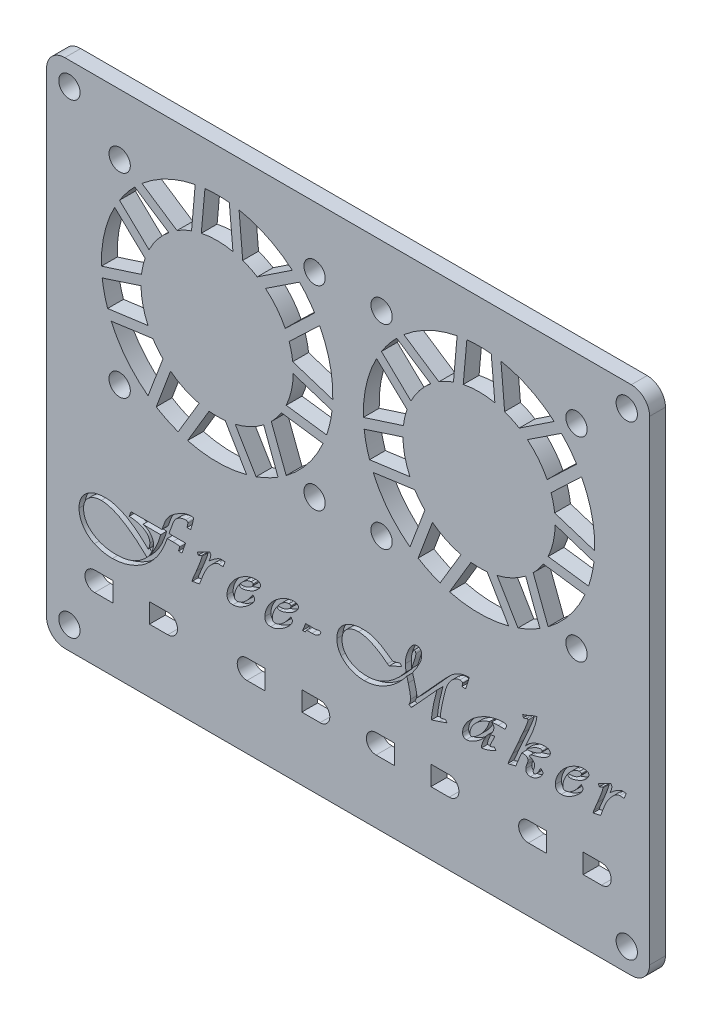
SolidWorks part; units mm, degrees
ref_plane "前基準面" through (0, 0, 0) normal (0, 0, 1) x (1, 0, 0)
ref_plane "上基準面" through (0, 0, 0) normal (0, 1, 0) x (1, 0, 0)
ref_plane "右基準面" through (0, 0, 0) normal (1, 0, 0) x (0, 0, -1)
sketch "草圖1" plane through (0, 0, 0) normal (0, 0, 1) x (1, 0, 0)
  line L0 (0, 42) -> (0, -42) construction
  line L1 (-46.5, 42) -> (46.5, 42)
  line L2 (-49.5, 39) -> (-49.5, -39)
  line L3 (-46.5, -42) -> (46.5, -42)
  line L4 (49.5, 39) -> (49.5, -39)
  line L5 (-49.5, 0) -> (49.5, 0) construction
  circle A0 centre (-45.75, 38.25) radius 1.75
  circle A1 centre (45.75, 38.25) radius 1.75
  circle A2 centre (45.75, -38.25) radius 1.75
  circle A3 centre (-45.75, -38.25) radius 1.75
  arc A4 (-46.5, -42) -> (-49.5, -39) centre (-46.5, -39) cw
  arc A5 (46.5, -42) -> (49.5, -39) centre (46.5, -39) ccw
  arc A6 (49.5, 39) -> (46.5, 42) centre (46.5, 39) ccw
  arc A7 (-46.5, 42) -> (-49.5, 39) centre (-46.5, 39) ccw
  point P4 (-49.5, 0)
  point P7 (0, -42)
  point P22 (-49.5, -42)
  point P27 (49.5, 42)
  point P30 (-49.5, 42)
  dimension "D3" = 3.5
  dimension "D6" = 3
  dimension "D1" = 99
  dimension "D2" = 84
  dimension "D4" = 3.75
  dimension "D5" = 3.75
extrude "填料-伸長1" add sketch "草圖1" along normal blind 2.6
sketch "草圖3" plane through (0, 0, 2.6) normal (0, 0, 1) x (1, 0, 0)
  line L1 (-37.5, 32) -> (-5.5, 32) construction
  line L2 (-37.5, 32) -> (-37.5, 0) construction
  line L3 (-37.5, 0) -> (-5.5, 0) construction
  line L4 (-5.5, 32) -> (-5.5, 0) construction
  line L5 (46.5, 42) -> (-46.5, 42) construction
  line L6 (-49.5, 39) -> (-49.5, -39) construction
  line L7 (0, 0) -> (0, 42) construction
  line L8 (-41.5, 36) -> (-1.5, 36) construction
  line L9 (-41.5, 36) -> (-41.5, -4) construction
  line L10 (-41.5, -4) -> (-1.5, -4) construction
  line L11 (-1.5, 36) -> (-1.5, -4) construction
  line L12 (1.5, 36) -> (1.5, -4) construction
  line L13 (41.5, -4) -> (1.5, -4) construction
  line L14 (41.5, 36) -> (41.5, -4) construction
  line L15 (41.5, 36) -> (1.5, 36) construction
  line L16 (5.5, 32) -> (5.5, 0) construction
  line L17 (37.5, 0) -> (5.5, 0) construction
  line L18 (37.5, 32) -> (37.5, 0) construction
  line L19 (37.5, 32) -> (5.5, 32) construction
  circle A0 centre (-37.5, 32) radius 1.75
  circle A1 centre (-5.5, 32) radius 1.75
  circle A2 centre (-5.5, 0) radius 1.75
  circle A3 centre (-37.5, 0) radius 1.75
  circle A4 centre (5.5, 0) radius 1.75
  circle A5 centre (37.5, 0) radius 1.75
  circle A6 centre (5.5, 32) radius 1.75
  circle A7 centre (37.5, 32) radius 1.75
  point P16 (-21.5, 32)
  point P32 (-21.5, 16)
  dimension "D6" = 3.5
  dimension "D7" = 3.5
  dimension "D8" = 3.5
  dimension "D9" = 3.5
  dimension "D1" = 32
  dimension "D2" = 32
  dimension "D3" = 10
  dimension "D4" = 12
  dimension "D5" = 4
  dimension "D10" = 4
  dimension "D11" = 4
  dimension "D12" = 4
extrude "除料-伸長2" cut sketch "草圖3" against normal through all
sketch "草圖4" plane through (0, 0, 2.6) normal (0, 0, 1) x (1, 0, 0)
  line L0 (-21.5, 35) -> (-21.5, 16) construction
  line L1 (-25.1, 34.6558) -> (-25.7, 27.7733)
  line L2 (-23.5, 34.8944) -> (-24.1, 28.2266)
  line L3 (-19.5, 34.8944) -> (-18.9, 28.2266)
  line L4 (-17.9, 34.6558) -> (-17.3, 27.7733)
  line L5 (-4.6697, 24.8171) -> (-9.6766, 20.0568)
  line L6 (-5.4807, 26.2168) -> (-10.3198, 21.5904)
  line L7 (-7.9747, 29.3442) -> (-13.5619, 25.6559)
  line L8 (-9.1588, 30.4463) -> (-14.9139, 26.6242)
  line L9 (-4.113, 8.3389) -> (-10.9565, 9.2855)
  line L10 (-3.5243, 9.8457) -> (-10.1585, 10.7445)
  line L11 (-2.6342, 13.7454) -> (-9.0014, 15.8141)
  line L12 (-2.5108, 15.3584) -> (-9.0873, 17.4749)
  line L13 (-16.649, -2.3703) -> (-20.1758, 3.5703)
  line L14 (-15.1039, -1.8911) -> (-18.5376, 3.8561)
  line L15 (-11.5001, -0.1555) -> (-13.8526, 6.1123)
  line L16 (-10.1621, 0.7537) -> (-12.6077, 7.215)
  line L17 (-32.8379, 0.7537) -> (-30.3923, 7.215)
  line L18 (-31.4999, -0.1555) -> (-29.1474, 6.1123)
  line L19 (-27.8961, -1.8911) -> (-24.4624, 3.8561)
  line L20 (-26.351, -2.3703) -> (-22.8242, 3.5703)
  line L21 (-40.4892, 15.3584) -> (-33.9127, 17.4749)
  line L22 (-40.3658, 13.7454) -> (-33.9986, 15.8141)
  line L23 (-39.4757, 9.8457) -> (-32.8415, 10.7445)
  line L24 (-38.887, 8.3389) -> (-32.0435, 9.2855)
  line L25 (-33.8412, 30.4463) -> (-28.0861, 26.6242)
  line L26 (-35.0253, 29.3442) -> (-29.4381, 25.6559)
  line L27 (-37.5193, 26.2168) -> (-32.6802, 21.5904)
  line L28 (-38.3303, 24.8171) -> (-33.3234, 20.0568)
  line L29 (0, 0) -> (0, 42) construction
  line L30 (46.5, 42) -> (-46.5, 42) construction
  line L31 (21.5, 35) -> (21.5, 16) construction
  line L32 (38.3303, 24.8171) -> (33.3234, 20.0568)
  line L33 (37.5193, 26.2168) -> (32.6802, 21.5904)
  line L34 (35.0253, 29.3442) -> (29.4381, 25.6559)
  line L35 (33.8412, 30.4463) -> (28.0861, 26.6242)
  line L36 (38.887, 8.3389) -> (32.0435, 9.2855)
  line L37 (39.4757, 9.8457) -> (32.8415, 10.7445)
  line L38 (40.3658, 13.7454) -> (33.9986, 15.8141)
  line L39 (40.4892, 15.3584) -> (33.9127, 17.4749)
  line L40 (26.351, -2.3703) -> (22.8242, 3.5703)
  line L41 (27.8961, -1.8911) -> (24.4624, 3.8561)
  line L42 (31.4999, -0.1555) -> (29.1474, 6.1123)
  line L43 (32.8379, 0.7537) -> (30.3923, 7.215)
  line L44 (10.1621, 0.7537) -> (12.6077, 7.215)
  line L45 (11.5001, -0.1555) -> (13.8526, 6.1123)
  line L46 (15.1039, -1.8911) -> (18.5376, 3.8561)
  line L47 (16.649, -2.3703) -> (20.1758, 3.5703)
  line L48 (2.5108, 15.3584) -> (9.0873, 17.4749)
  line L49 (2.6342, 13.7454) -> (9.0014, 15.8141)
  line L50 (3.5243, 9.8457) -> (10.1585, 10.7445)
  line L51 (4.113, 8.3389) -> (10.9565, 9.2855)
  line L52 (9.1588, 30.4463) -> (14.9139, 26.6242)
  line L53 (7.9747, 29.3442) -> (13.5619, 25.6559)
  line L54 (5.4807, 26.2168) -> (10.3198, 21.5904)
  line L55 (4.6697, 24.8171) -> (9.6766, 20.0568)
  line L56 (17.9, 34.6558) -> (17.3, 27.7733)
  line L57 (19.5, 34.8944) -> (18.9, 28.2266)
  line L58 (23.5, 34.8944) -> (24.1, 28.2266)
  line L59 (25.1, 34.6558) -> (25.7, 27.7733)
  arc A0 (-31.4999, -0.1555) -> (-27.8961, -1.8911) centre (-21.5, 16) ccw
  arc A1 (-29.1474, 6.1123) -> (-24.4624, 3.8561) centre (-21.5, 16) ccw
  arc A2 (-32.0435, 9.2855) -> (-30.3923, 7.215) centre (-21.5, 16) ccw
  arc A3 (-38.887, 8.3389) -> (-32.8379, 0.7537) centre (-21.5, 16) ccw
  arc A4 (-33.9986, 15.8141) -> (-32.8415, 10.7445) centre (-21.5, 16) ccw
  arc A5 (-40.3658, 13.7454) -> (-39.4757, 9.8457) centre (-21.5, 16) ccw
  arc A6 (-33.3234, 20.0568) -> (-33.9127, 17.4749) centre (-21.5, 16) ccw
  arc A7 (-38.3303, 24.8171) -> (-40.4892, 15.3584) centre (-21.5, 16) ccw
  arc A8 (-35.0253, 29.3442) -> (-37.5193, 26.2168) centre (-21.5, 16) ccw
  arc A9 (-29.4381, 25.6559) -> (-32.6802, 21.5904) centre (-21.5, 16) ccw
  arc A10 (-25.7, 27.7733) -> (-28.0861, 26.6242) centre (-21.5, 16) ccw
  arc A11 (-25.1, 34.6558) -> (-33.8412, 30.4463) centre (-21.5, 16) ccw
  arc A12 (-19.5, 34.8944) -> (-23.5, 34.8944) centre (-21.5, 16) ccw
  arc A13 (-18.9, 28.2266) -> (-24.1, 28.2266) centre (-21.5, 16) ccw
  arc A14 (-9.1588, 30.4463) -> (-17.9, 34.6558) centre (-21.5, 16) ccw
  arc A15 (-14.9139, 26.6242) -> (-17.3, 27.7733) centre (-21.5, 16) ccw
  arc A16 (-10.3198, 21.5904) -> (-13.5619, 25.6559) centre (-21.5, 16) ccw
  arc A17 (-5.4807, 26.2168) -> (-7.9747, 29.3442) centre (-21.5, 16) ccw
  arc A18 (-9.0873, 17.4749) -> (-9.6766, 20.0568) centre (-21.5, 16) ccw
  arc A19 (-2.5108, 15.3584) -> (-4.6697, 24.8171) centre (-21.5, 16) ccw
  arc A20 (-10.1585, 10.7445) -> (-9.0014, 15.8141) centre (-21.5, 16) ccw
  arc A21 (-3.5243, 9.8457) -> (-2.6342, 13.7454) centre (-21.5, 16) ccw
  arc A22 (-12.6077, 7.215) -> (-10.9565, 9.2855) centre (-21.5, 16) ccw
  arc A23 (-10.1621, 0.7537) -> (-4.113, 8.3389) centre (-21.5, 16) ccw
  arc A24 (-15.1039, -1.8911) -> (-11.5001, -0.1555) centre (-21.5, 16) ccw
  arc A25 (-18.5376, 3.8561) -> (-13.8526, 6.1123) centre (-21.5, 16) ccw
  arc A26 (-22.8242, 3.5703) -> (-20.1758, 3.5703) centre (-21.5, 16) ccw
  arc A27 (-26.351, -2.3703) -> (-16.649, -2.3703) centre (-21.5, 16) ccw
  arc A28 (26.351, -2.3703) -> (16.649, -2.3703) centre (21.5, 16) cw
  arc A29 (22.8242, 3.5703) -> (20.1758, 3.5703) centre (21.5, 16) cw
  arc A30 (18.5376, 3.8561) -> (13.8526, 6.1123) centre (21.5, 16) cw
  arc A31 (15.1039, -1.8911) -> (11.5001, -0.1555) centre (21.5, 16) cw
  arc A32 (10.1621, 0.7537) -> (4.113, 8.3389) centre (21.5, 16) cw
  arc A33 (12.6077, 7.215) -> (10.9565, 9.2855) centre (21.5, 16) cw
  arc A34 (3.5243, 9.8457) -> (2.6342, 13.7454) centre (21.5, 16) cw
  arc A35 (10.1585, 10.7445) -> (9.0014, 15.8141) centre (21.5, 16) cw
  arc A36 (2.5108, 15.3584) -> (4.6697, 24.8171) centre (21.5, 16) cw
  arc A37 (9.0873, 17.4749) -> (9.6766, 20.0568) centre (21.5, 16) cw
  arc A38 (5.4807, 26.2168) -> (7.9747, 29.3442) centre (21.5, 16) cw
  arc A39 (10.3198, 21.5904) -> (13.5619, 25.6559) centre (21.5, 16) cw
  arc A40 (14.9139, 26.6242) -> (17.3, 27.7733) centre (21.5, 16) cw
  arc A41 (9.1588, 30.4463) -> (17.9, 34.6558) centre (21.5, 16) cw
  arc A42 (18.9, 28.2266) -> (24.1, 28.2266) centre (21.5, 16) cw
  arc A43 (19.5, 34.8944) -> (23.5, 34.8944) centre (21.5, 16) cw
  arc A44 (25.1, 34.6558) -> (33.8412, 30.4463) centre (21.5, 16) cw
  arc A45 (25.7, 27.7733) -> (28.0861, 26.6242) centre (21.5, 16) cw
  arc A46 (29.4381, 25.6559) -> (32.6802, 21.5904) centre (21.5, 16) cw
  arc A47 (35.0253, 29.3442) -> (37.5193, 26.2168) centre (21.5, 16) cw
  arc A48 (38.3303, 24.8171) -> (40.4892, 15.3584) centre (21.5, 16) cw
  arc A49 (33.3234, 20.0568) -> (33.9127, 17.4749) centre (21.5, 16) cw
  arc A50 (40.3658, 13.7454) -> (39.4757, 9.8457) centre (21.5, 16) cw
  arc A51 (33.9986, 15.8141) -> (32.8415, 10.7445) centre (21.5, 16) cw
  arc A52 (38.887, 8.3389) -> (32.8379, 0.7537) centre (21.5, 16) cw
  arc A53 (32.0435, 9.2855) -> (30.3923, 7.215) centre (21.5, 16) cw
  arc A54 (29.1474, 6.1123) -> (24.4624, 3.8561) centre (21.5, 16) cw
  arc A55 (31.4999, -0.1555) -> (27.8961, -1.8911) centre (21.5, 16) cw
  point P63 (-21.5, 16)
  dimension "D1" = 38
  dimension "D2" = 25
  dimension "D3" = 2
  dimension "D4" = 3.6
  dimension "D5" = 2.6
  dimension "D6" = 4.2
  dimension "D7" = 7
extrude "除料-伸長3" cut sketch "草圖4" against normal through all
sketch "草圖5" plane through (0, 0, 2.6) normal (0, 0, 1) x (1, 0, 0)
  line L0 (-16.6, -30) -> (-4.6, -30) construction
  line L1 (-16.6, -28.4) -> (-13.6, -28.4)
  line L2 (-16.6, -31.6) -> (-13.6, -31.6)
  line L3 (-13.6, -28.4) -> (-13.6, -31.6)
  line L4 (-7.6, -31.6) -> (-4.6, -31.6)
  line L5 (-7.6, -28.4) -> (-7.6, -31.6)
  line L6 (-7.6, -28.4) -> (-4.6, -28.4)
  line L7 (-41.6, -28.4) -> (-38.6, -28.4)
  line L8 (-41.6, -31.6) -> (-38.6, -31.6)
  line L9 (-38.6, -28.4) -> (-38.6, -31.6)
  line L10 (-32.6, -31.6) -> (-29.6, -31.6)
  line L11 (-32.6, -28.4) -> (-32.6, -31.6)
  line L12 (-32.6, -28.4) -> (-29.6, -28.4)
  line L13 (-41.6, -30) -> (-29.6, -30) construction
  line L14 (-7.6, -31.6) -> (-4.6, -31.6)
  line L15 (-7.6, -28.4) -> (-4.6, -28.4)
  line L16 (-16.6, -28.4) -> (-13.6, -28.4)
  line L17 (-16.6, -31.6) -> (-13.6, -31.6)
  line L18 (0, 0) -> (0, -42) construction
  line L19 (-46.5, -42) -> (46.5, -42) construction
  line L20 (41.6, -30) -> (29.6, -30) construction
  line L21 (16.6, -30) -> (4.6, -30) construction
  line L22 (16.6, -31.6) -> (13.6, -31.6)
  line L23 (16.6, -28.4) -> (13.6, -28.4)
  line L24 (7.6, -28.4) -> (4.6, -28.4)
  line L25 (7.6, -31.6) -> (4.6, -31.6)
  line L26 (32.6, -28.4) -> (29.6, -28.4)
  line L27 (32.6, -28.4) -> (32.6, -31.6)
  line L28 (32.6, -31.6) -> (29.6, -31.6)
  line L29 (38.6, -28.4) -> (38.6, -31.6)
  line L30 (41.6, -31.6) -> (38.6, -31.6)
  line L31 (41.6, -28.4) -> (38.6, -28.4)
  line L32 (7.6, -28.4) -> (4.6, -28.4)
  line L33 (7.6, -28.4) -> (7.6, -31.6)
  line L34 (7.6, -31.6) -> (4.6, -31.6)
  line L35 (13.6, -28.4) -> (13.6, -31.6)
  line L36 (16.6, -31.6) -> (13.6, -31.6)
  line L37 (16.6, -28.4) -> (13.6, -28.4)
  arc A0 (-16.6, -28.4) -> (-16.6, -31.6) centre (-16.6, -30) ccw
  arc A1 (-4.6, -31.6) -> (-4.6, -28.4) centre (-4.6, -30) ccw
  arc A2 (-41.6, -28.4) -> (-41.6, -31.6) centre (-41.6, -30) ccw
  arc A3 (-29.6, -31.6) -> (-29.6, -28.4) centre (-29.6, -30) ccw
  arc A4 (29.6, -31.6) -> (29.6, -28.4) centre (29.6, -30) cw
  arc A5 (41.6, -28.4) -> (41.6, -31.6) centre (41.6, -30) cw
  arc A6 (4.6, -31.6) -> (4.6, -28.4) centre (4.6, -30) cw
  arc A7 (16.6, -28.4) -> (16.6, -31.6) centre (16.6, -30) cw
  point P2 (-10.6, -30)
  point P15 (-35.6, -30)
  point P47 (35.6, -30)
  point P48 (10.6, -30)
  dimension "D1" = 4.6
  dimension "D2" = 12
  dimension "D3" = 3.2
  dimension "D4" = 3
  dimension "D5" = 3
  dimension "D7" = 30
  dimension "D6" = 2
extrude "除料-伸長4" cut sketch "草圖5" against normal through all contours L7 A2 L8 L9 | L10 A3 L12 L11 | L1 A0 L2 L3 | L4 A1 L6 L5 | A6 L25 L33 L24 | A7 L23 L35 L22 | A4 L28 L27 L26 | A5 L31 L29 L30 region at (-15.7433, -30, 2.6) region at (-5.4567, -30, 2.6) region at (-40.7433, -30, 2.6) region at (-30.4567, -30, 2.6) region at (15.7433, -30, 2.6) region at (5.4567, -30, 2.6) region at (30.4567, -30, 2.6) region at (40.7433, -30, 2.6)
sketch "草圖6" plane through (0, 0, 2.6) normal (0, 0, 1) x (1, 0, 0)
  line L0 (-49.5, -22) -> (49.5, -22) construction
  line L1 (-49.5, 39) -> (-49.5, -39) construction
  line L2 (49.5, -39) -> (49.5, 39) construction
  line L3 (-46.5, -42) -> (46.5, -42) construction
  line L4 (-26.69, -17.1082) -> (-27.2499, -18.8203)
  line L5 (-27.2499, -18.8203) -> (-27.8365, -18.8203)
  line L6 (-28.79, -17.9642) -> (-29.692, -17.9642)
  line L7 (-29.692, -17.9642) -> (-29.7646, -18.1591)
  line L8 (-32.929, -20.8993) -> (-32.8488, -21.0656)
  line L9 (-35.6233, -17.1254) -> (-30.5404, -17.1082)
  line L10 (-25.7689, -14.5323) -> (-25.8435, -14.7845)
  line L11 (-25.8435, -14.7845) -> (-26.4397, -14.7845)
  line L12 (-29.1187, -16.317) -> (-29.3874, -17.1082)
  line L14 (-29.3874, -17.1082) -> (-26.69, -17.1082)
  line L15 (-30.7754, -17.9642) -> (-33.6838, -17.947)
  line L16 (-20.206, -16.5483) -> (-20.527, -17.4005)
  line L17 (-24.2915, -21.5013) -> (-24.387, -21.7631)
  line L18 (-25.61, -22.0134) -> (-25.524, -21.6541)
  line L19 (-25.524, -21.6541) -> (-24.8934, -20.1636)
  line L20 (-24.6029, -17.7922) -> (-24.773, -17.4139)
  line L22 (-6.9663, -18.698) -> (-5.9134, -18.698)
  line L23 (-5.9134, -18.698) -> (-5.6268, -18.698)
  line L24 (-4.5624, -18.6216) -> (-4.4554, -18.7439)
  line L25 (-4.4554, -18.7439) -> (-4.4955, -18.8279)
  line L26 (-5.9344, -19.5541) -> (-6.2726, -19.5541)
  line L27 (-6.2726, -19.5541) -> (-6.63, -19.5541)
  line L28 (-6.9529, -19.7776) -> (-7.0313, -19.921)
  line L29 (-7.0313, -19.921) -> (-7.4612, -19.921)
  line L30 (-7.4612, -19.921) -> (-6.9663, -18.698)
  line L31 (19.9048, -12.9272) -> (19.2876, -14.8533)
  line L32 (19.2876, -14.8533) -> (18.7067, -14.7979)
  line L33 (18.7067, -14.7979) -> (18.7621, -14.5246)
  line L34 (15.9818, -20.8497) -> (16.2283, -21.2146)
  line L36 (13.7786, -18.2623) -> (12.2155, -19.9802)
  line L37 (12.2155, -19.9802) -> (10.6256, -21.7153)
  line L38 (10.6256, -21.7153) -> (10.3657, -21.9312)
  line L39 (10.3657, -21.9312) -> (9.9855, -21.7325)
  line L40 (9.8785, -18.7114) -> (9.6492, -17.8649)
  line L41 (8.516, -16.5674) -> (8.7912, -16.9075)
  line L42 (8.7912, -16.9075) -> (6.7351, -17.8821)
  line L43 (6.7351, -17.8821) -> (6.4695, -17.7043)
  line L44 (11.3529, -20.0755) -> (11.7932, -19.5942)
  line L45 (11.7932, -19.5942) -> (15.141, -15.9139)
  line L46 (24.0174, -20.7866) -> (24.2888, -21.0904)
  line L47 (24.0652, -19.1834) -> (23.9773, -19.4719)
  line L48 (30.553, -20.4407) -> (30.4212, -20.8363)
  line L49 (28.2619, -19.9401) -> (28.046, -20.4273)
  line L50 (27.5988, -21.5165) -> (27.5319, -21.7)
  line L51 (26.5574, -21.9522) -> (26.2344, -21.9943)
  line L52 (27.037, -20.1598) -> (27.8434, -18.3407)
  line L53 (27.8434, -18.3407) -> (28.7148, -16.3572)
  line L54 (29.2345, -14.089) -> (29.0606, -14.1597)
  line L55 (28.7778, -14.2132) -> (28.6632, -13.8119)
  line L56 (30.5549, -13.0514) -> (30.9925, -12.9654)
  line L59 (45.6383, -16.5483) -> (45.3172, -17.4005)
  line L60 (41.5528, -21.5013) -> (41.4573, -21.7631)
  line L61 (40.2343, -22.0134) -> (40.3203, -21.6541)
  line L62 (40.3203, -21.6541) -> (40.9509, -20.1636)
  line L63 (41.2413, -17.7922) -> (41.0713, -17.4139)
  spline S0 degree 3 poles (-27.8365, -18.8203) (-27.8201, -18.7474) (-27.7934, -18.6397) (-27.7682, -18.5313) (-27.7544, -18.4974) knots 0 0 0 0 0.671438 1 1 1 1
  spline S1 degree 3 poles (-27.7544, -18.4974) (-27.7243, -18.4367) (-27.6765, -18.3309) (-27.651, -18.217) (-27.6512, -18.1687) knots 0 0 0 0 0.585177 1 1 1 1
  spline S2 degree 3 poles (-27.6512, -18.1687) (-27.6477, -18.1306) (-27.6754, -18.0751) (-27.7456, -18.0279) (-27.8074, -18.0086) (-27.8732, -17.9973) (-27.9446, -17.9875) (-28.0358, -17.9805) (-28.148, -17.9753) (-28.2798, -17.9692) (-28.4964, -17.9642) (-28.6684, -17.9636) (-28.79, -17.9642) knots 0 0 0 0 0.089513 0.140958 0.20354 0.246327 0.304505 0.379559 0.470057 0.579232 0.702371 1 1 1 1
  spline S3 degree 3 poles (-29.7646, -18.1591) (-29.8619, -18.4321) (-30.0137, -18.8316) (-30.2313, -19.3488) (-30.3976, -19.7139) (-30.5688, -20.0635) (-30.7474, -20.3961) (-30.9282, -20.7133) (-31.1151, -21.0163) (-31.311, -21.3086) (-31.5196, -21.5934) (-31.7413, -21.8727) (-31.9774, -22.146) (-32.2252, -22.4163) (-32.5802, -22.7691) (-32.86, -23.0238) (-33.0532, -23.1886) knots 0 0 0 0 0.142763 0.210559 0.276433 0.340441 0.402364 0.462394 0.520318 0.577771 0.635715 0.694242 0.753443 0.813637 0.874892 1 1 1 1
  spline S4 degree 3 poles (-33.0532, -23.1886) (-33.242, -23.3505) (-33.5364, -23.5822) (-33.9504, -23.8641) (-34.2737, -24.063) (-34.6093, -24.2488) (-34.9566, -24.4216) (-35.3147, -24.5855) (-35.6836, -24.7331) (-36.0579, -24.8659) (-36.4334, -24.984) (-36.8095, -25.0804) (-37.1849, -25.1612) (-37.5596, -25.2249) (-38.0582, -25.2826) (-38.4332, -25.3017) (-38.6827, -25.302) knots 0 0 0 0 0.121614 0.183048 0.244865 0.307196 0.370585 0.434575 0.499712 0.564841 0.628787 0.69218 0.754625 0.816542 0.878019 1 1 1 1
  spline S5 degree 3 poles (-38.6827, -25.302) (-38.9498, -25.3011) (-39.3473, -25.2857) (-39.8668, -25.2172) (-40.2436, -25.1515) (-40.6088, -25.063) (-41.0819, -24.9237) (-41.4234, -24.7866) (-41.6445, -24.6829) knots 0 0 0 0 0.262867 0.390457 0.515187 0.638873 0.759782 1 1 1 1
  spline S6 degree 3 poles (-41.6445, -24.6829) (-41.838, -24.5941) (-42.1154, -24.4413) (-42.4611, -24.2067) (-42.7029, -24.0197) (-42.9273, -23.8167) (-43.1334, -23.5976) (-43.3261, -23.3665) (-43.4981, -23.1197) (-43.6566, -22.865) (-43.7888, -22.5982) (-43.9045, -22.3269) (-43.9989, -22.0478) (-44.0712, -21.7615) (-44.14, -21.3665) (-44.1636, -21.0645) (-44.1611, -20.8611) knots 0 0 0 0 0.131798 0.195709 0.258692 0.320984 0.382945 0.444882 0.507171 0.569157 0.630564 0.691388 0.751779 0.812834 0.874135 1 1 1 1
  spline S7 degree 3 poles (-44.1611, -20.8611) (-44.1608, -20.5978) (-44.1265, -20.2098) (-44.003, -19.715) (-43.8713, -19.3735) (-43.7067, -19.0501) (-43.5009, -18.7505) (-43.2593, -18.4705) (-42.983, -18.2136) (-42.675, -17.9838) (-42.344, -17.7797) (-41.987, -17.6089) (-41.6069, -17.4698) (-41.2022, -17.3635) (-40.6201, -17.2558) (-40.1661, -17.2313) (-39.8579, -17.2304) knots 0 0 0 0 0.124637 0.183439 0.240897 0.29754 0.354832 0.412561 0.472302 0.533033 0.594214 0.656119 0.720037 0.785574 0.853946 1 1 1 1
  spline S8 degree 3 poles (-39.8579, -17.2304) (-39.4786, -17.233) (-38.9016, -17.2879) (-38.1427, -17.4751) (-37.5588, -17.6687) (-36.9695, -17.9215) (-36.1548, -18.3411) (-35.5629, -18.7225) (-35.1762, -19.0057) knots 0 0 0 0 0.223587 0.339883 0.460164 0.585838 0.717494 1 1 1 1
  spline S9 degree 3 poles (-35.1762, -19.0057) (-35.0181, -19.1228) (-34.7722, -19.3074) (-34.4415, -19.5758) (-34.1682, -19.8032) (-33.8798, -20.0499) (-33.4627, -20.4147) (-33.1452, -20.7013) (-32.929, -20.8993) knots 0 0 0 0 0.200841 0.313612 0.434525 0.563603 0.700864 1 1 1 1
  spline S10 degree 3 poles (-32.8488, -21.0656) (-32.7494, -20.9148) (-32.5928, -20.5843) (-32.5426, -20.222) (-32.543, -20.0414) knots 0 0 0 0 0.499901 1 1 1 1
  spline S11 degree 3 poles (-32.543, -20.0414) (-32.5421, -19.9016) (-32.569, -19.6918) (-32.6656, -19.4289) (-32.7634, -19.2399) (-32.8912, -19.0609) (-33.0482, -18.8928) (-33.2305, -18.7312) (-33.4414, -18.5816) (-33.6752, -18.4421) (-33.9335, -18.3199) (-34.2129, -18.2135) (-34.5148, -18.1215) (-34.8385, -18.0457) (-35.3129, -17.9653) (-35.6816, -17.9311) (-35.9348, -17.9203) knots 0 0 0 0 0.095361 0.142504 0.190505 0.240054 0.29202 0.347118 0.40596 0.468105 0.532626 0.600568 0.671899 0.747779 0.827138 1 1 1 1
  spline S12 degree 2 poles (-35.9348, -17.9203) (-35.7553, -17.5321) (-35.6233, -17.1254) knots 0 0 0 1 1 1
  spline S13 degree 2 poles (-30.5404, -17.1082) (-30.5123, -17.0267) (-30.4831, -16.9457) knots 0 0 0 1 1 1
  spline S14 degree 3 poles (-30.4831, -16.9457) (-30.4335, -16.7943) (-30.3593, -16.5764) (-30.2625, -16.2971) (-30.1924, -16.1146) (-30.1309, -15.9472) (-30.0685, -15.7992) (-30.0145, -15.6661) (-29.9422, -15.5136) (-29.8517, -15.3344) (-29.6808, -15.0642) (-29.5357, -14.872) (-29.4283, -14.752) knots 0 0 0 0 0.194852 0.281573 0.36144 0.433922 0.499596 0.5579 0.609477 0.705984 0.803253 1 1 1 1
  spline S15 degree 3 poles (-29.4283, -14.752) (-29.2126, -14.5082) (-28.6962, -14.0311) (-28.1076, -13.6471) (-27.7849, -13.4565) knots 0 0 0 0 0.464399 1 1 1 1
  spline S16 degree 3 poles (-27.7849, -13.4565) (-27.6156, -13.3589) (-27.366, -13.2213) (-27.0278, -13.0747) (-26.7934, -12.9835) (-26.5675, -12.9138) (-26.2869, -12.8528) (-26.0798, -12.8258) (-25.9448, -12.8278) knots 0 0 0 0 0.298373 0.434182 0.562176 0.682097 0.794595 1 1 1 1
  spline S17 degree 3 poles (-25.9448, -12.8278) (-25.8709, -12.8282) (-25.6676, -12.8268) (-25.4646, -12.8156) (-25.3352, -12.8144) knots 0 0 0 0 0.363549 1 1 1 1
  spline S18 degree 3 poles (-25.3352, -12.8144) (-25.3535, -12.9328) (-25.3871, -13.1163) (-25.4451, -13.3675) (-25.4936, -13.5764) (-25.554, -13.7969) (-25.6434, -14.1179) (-25.7144, -14.3648) (-25.7689, -14.5323) knots 0 0 0 0 0.202714 0.315388 0.436141 0.565528 0.702004 1 1 1 1
  spline S19 degree 3 poles (-26.4397, -14.7845) (-26.4026, -14.6362) (-26.3492, -14.4067) (-26.3078, -14.1741) (-26.3059, -14.0909) knots 0 0 0 0 0.648172 1 1 1 1
  spline S20 degree 3 poles (-26.3059, -14.0909) (-26.3053, -14.0485) (-26.3155, -13.9865) (-26.3552, -13.9149) (-26.3988, -13.8747) (-26.4529, -13.8431) (-26.5458, -13.8114) (-26.6241, -13.8054) (-26.6785, -13.8062) knots 0 0 0 0 0.23733 0.344538 0.453164 0.565257 0.694033 1 1 1 1
  spline S21 degree 3 poles (-26.6785, -13.8062) (-26.7901, -13.8054) (-26.9585, -13.8235) (-27.181, -13.8709) (-27.3507, -13.9228) (-27.5203, -13.9929) (-27.754, -14.1043) (-27.9242, -14.2058) (-28.0333, -14.2839) knots 0 0 0 0 0.229153 0.347096 0.467688 0.593462 0.724135 1 1 1 1
  spline S22 degree 3 poles (-28.0333, -14.2839) (-28.1335, -14.355) (-28.2749, -14.4818) (-28.4305, -14.6857) (-28.5242, -14.8303) (-28.5927, -14.967) (-28.6554, -15.0911) (-28.7188, -15.2398) (-28.7877, -15.4116) (-28.864, -15.6048) (-28.9764, -15.909) (-29.0601, -16.1493) (-29.1187, -16.317) knots 0 0 0 0 0.157422 0.241154 0.328082 0.377717 0.436834 0.506265 0.584603 0.674005 0.772374 1 1 1 1
  spline S23 degree 3 poles (-33.6838, -17.947) (-33.5646, -17.965) (-33.3896, -18.0105) (-33.1682, -18.1034) (-33.0094, -18.1874) (-32.857, -18.2878) (-32.7121, -18.4046) (-32.5735, -18.5376) (-32.4441, -18.6848) (-32.3255, -18.8398) (-32.2188, -18.9963) (-32.1315, -19.1556) (-32.0573, -19.3145) (-32.002, -19.4762) (-31.9488, -19.6913) (-31.9303, -19.8558) (-31.9315, -19.9649) knots 0 0 0 0 0.125442 0.187264 0.249556 0.312271 0.376892 0.443019 0.512074 0.580643 0.646115 0.70904 0.769571 0.828497 0.886555 1 1 1 1
  spline S24 degree 3 poles (-31.9315, -19.9649) (-31.9321, -20.1421) (-31.9704, -20.4143) (-32.0784, -20.7761) (-32.1968, -21.0649) (-32.3465, -21.3649) (-32.5145, -21.6507) (-32.6368, -21.8331) (-32.6942, -21.915) knots 0 0 0 0 0.202262 0.312421 0.43104 0.558728 0.695515 0.809828 0.809828 0.809828 0.809828
  spline S25 degree 3 poles (-33.0185, -22.2894) (-33.1878, -22.1238) (-33.5331, -21.7951) (-34.0575, -21.3201) (-34.5803, -20.8666) (-35.0952, -20.4454) (-35.6009, -20.0549) (-36.0995, -19.6975) (-36.5896, -19.3718) (-37.0695, -19.0772) (-37.5404, -18.8174) (-37.9986, -18.5875) (-38.4479, -18.3973) (-38.8841, -18.2381) (-39.3099, -18.1183) (-39.8502, -18.0003) (-40.256, -17.965) (-40.5209, -17.9642) knots 0.004157 0.004157 0.004157 0.004157 0.084118 0.165115 0.243026 0.317761 0.389682 0.458732 0.524821 0.588334 0.648785 0.706396 0.76132 0.813428 0.863057 0.910551 1 1 1 1
  spline S26 degree 3 poles (-40.5209, -17.9642) (-40.7196, -17.9652) (-41.0136, -17.9841) (-41.3928, -18.0587) (-41.6592, -18.1376) (-41.9136, -18.2371) (-42.1544, -18.3599) (-42.3834, -18.5036) (-42.596, -18.6693) (-42.7906, -18.8517) (-42.9626, -19.0491) (-43.1059, -19.262) (-43.2241, -19.4882) (-43.3157, -19.7274) (-43.4048, -20.0708) (-43.426, -20.3406) (-43.4274, -20.5229) knots 0 0 0 0 0.137505 0.203094 0.266951 0.329465 0.391737 0.453717 0.516208 0.577928 0.63791 0.696938 0.755079 0.814079 0.873715 1 1 1 1
  spline S27 degree 3 poles (-43.4274, -20.5229) (-43.4299, -20.8019) (-43.3821, -21.2152) (-43.2216, -21.7391) (-43.0541, -22.1066) (-42.8382, -22.4533) (-42.573, -22.7773) (-42.2635, -23.0836) (-41.9064, -23.3629) (-41.5148, -23.6182) (-41.0928, -23.8398) (-40.6454, -24.0281) (-40.1718, -24.1797) (-39.6734, -24.3015) (-38.9588, -24.413) (-38.4066, -24.447) (-38.0311, -24.4459) knots 0 0 0 0 0.112418 0.166442 0.220347 0.274796 0.330672 0.388788 0.450039 0.513155 0.577033 0.641953 0.708636 0.777346 0.848621 1 1 1 1
  spline S28 degree 3 poles (-38.0311, -24.4459) (-37.8109, -24.4486) (-37.4843, -24.4316) (-37.0535, -24.39) (-36.7402, -24.3407) (-36.4326, -24.2827) (-36.1318, -24.2093) (-35.8367, -24.124) (-35.5491, -24.022) (-35.267, -23.9093) (-34.9918, -23.7835) (-34.7234, -23.6427) (-34.4599, -23.4909) (-34.2043, -23.324) (-33.9541, -23.146) (-33.7119, -22.9524) (-33.3952, -22.6767) (-33.1676, -22.4507) (-33.0211, -22.2923) (-33.0185, -22.2894) knots 0 0 0 0 0.062588 0.093007 0.123069 0.152781 0.182053 0.211127 0.240126 0.26883 0.297536 0.326147 0.355053 0.384005 0.41297 0.442375 0.472174 0.532399 0.533516 0.533516 0.533516 0.533516
  spline S29 degree 3 poles (-20.527, -17.4005) (-20.6608, -17.3889) (-20.8805, -17.363) (-21.1015, -17.3555) (-21.1882, -17.3527) knots 0 0 0 0 0.607672 1 1 1 1
  spline S30 degree 3 poles (-21.1882, -17.3527) (-21.3088, -17.354) (-21.4972, -17.3915) (-21.7373, -17.5059) (-21.9334, -17.6254) (-22.1352, -17.7802) (-22.4313, -18.0413) (-22.6384, -18.2731) (-22.778, -18.4381) knots 0 0 0 0 0.18251 0.286659 0.401941 0.5302 0.671843 1 1 1 1
  spline S31 degree 3 poles (-22.778, -18.4381) (-22.9139, -18.6022) (-23.1047, -18.8657) (-23.3329, -19.2427) (-23.47, -19.4982) (-23.5787, -19.7204) (-23.6646, -19.9106) (-23.7558, -20.1223) (-23.8535, -20.356) (-23.9566, -20.6113) (-24.1038, -20.9953) (-24.2163, -21.2942) (-24.2915, -21.5013) knots 0 0 0 0 0.186065 0.283692 0.384771 0.439272 0.499785 0.567079 0.640659 0.721051 0.807545 1 1 1 1
  spline S32 degree 2 poles (-24.387, -21.7631) (-24.9994, -21.8835) (-25.61, -22.0134) knots 0 0 0 1 1 1
  spline S33 degree 3 poles (-24.8934, -20.1636) (-24.8239, -19.9949) (-24.7226, -19.7493) (-24.5924, -19.4305) (-24.5077, -19.2113) (-24.4271, -19.0072) (-24.3534, -18.8171) (-24.2899, -18.6399) (-24.2293, -18.4776) (-24.1789, -18.3285) (-24.1316, -18.1942) (-24.0938, -18.073) (-24.0637, -17.9656) (-24.0374, -17.8731) (-24.0167, -17.7771) (-24.0081, -17.711) (-24.0067, -17.6719) knots 0 0 0 0 0.206588 0.300707 0.38974 0.472614 0.549067 0.620458 0.685689 0.745198 0.79855 0.846893 0.888882 0.924736 0.955704 1 1 1 1
  spline S34 degree 2 poles (-24.0067, -17.6719) (-24.005, -17.5991) (-24.0774, -17.5973) knots 0 0 0 1 1 1
  spline S35 degree 3 poles (-24.0774, -17.5973) (-24.0908, -17.6013) (-24.1193, -17.6085) (-24.166, -17.6258) (-24.2248, -17.6469) (-24.2975, -17.6759) (-24.4267, -17.7219) (-24.5286, -17.7649) (-24.6029, -17.7922) knots 0 0 0 0 0.07444 0.15744 0.266349 0.408769 0.575919 1 1 1 1
  spline S36 degree 2 poles (-24.773, -17.4139) (-23.7318, -16.9482) (-22.7341, -16.3954) knots 0 0 0 1 1 1
  spline S37 degree 3 poles (-22.7341, -16.3954) (-22.6826, -16.4599) (-22.5993, -16.5592) (-22.5416, -16.6778) (-22.5392, -16.726) knots 0 0 0 0 0.636406 1 1 1 1
  spline S38 degree 3 poles (-22.5392, -16.726) (-22.539, -16.8193) (-22.5598, -16.9676) (-22.6138, -17.1729) (-22.6742, -17.3522) (-22.7454, -17.5409) (-22.8, -17.6684) (-22.828, -17.731) knots 0 0 0 0 0.1734 0.27753 0.394919 0.525539 0.653062 0.653062 0.653062 0.653062
  spline S39 degree 3 poles (-22.828, -17.731) (-22.7667, -17.6769) (-22.6422, -17.57) (-22.4576, -17.4142) (-22.2753, -17.2684) (-22.1006, -17.1354) (-21.9335, -17.0145) (-21.7755, -16.9052) (-21.6246, -16.8093) (-21.4807, -16.7272) (-21.3455, -16.6558) (-21.2174, -16.5979) (-21.0965, -16.554) (-20.9532, -16.5114) (-20.847, -16.4959) (-20.7793, -16.4967) knots 0.193936 0.193936 0.193936 0.193936 0.275358 0.357301 0.434469 0.507795 0.575927 0.639792 0.699094 0.75393 0.804713 0.851276 0.893816 0.932761 1 1 1 1
  spline S40 degree 3 poles (-20.7793, -16.4967) (-20.704, -16.4984) (-20.5123, -16.5103) (-20.3221, -16.5372) (-20.206, -16.5483) knots 0 0 0 0 0.392357 1 1 1 1
  spline S41 degree 3 poles (-15.6291, -18.9502) (-15.5525, -19.0307) (-15.439, -19.1617) (-15.3511, -19.3162) (-15.3482, -19.3821) knots 0 0 0 0 0.634051 1 1 1 1
  spline S42 degree 3 poles (-15.3482, -19.3821) (-15.3503, -19.492) (-15.3875, -19.6637) (-15.4951, -19.8833) (-15.6126, -20.0619) (-15.7598, -20.249) (-16.015, -20.5198) (-16.2349, -20.713) (-16.3934, -20.842) knots 0 0 0 0 0.178109 0.281365 0.395936 0.524955 0.667787 1 1 1 1
  spline S43 degree 3 poles (-16.3934, -20.842) (-16.6158, -21.0215) (-16.9482, -21.2703) (-17.4055, -21.5465) (-17.7261, -21.7101) (-18.0355, -21.8408) (-18.4264, -21.9569) (-18.7201, -22.0027) (-18.912, -22) knots 0 0 0 0 0.303797 0.440438 0.567286 0.685958 0.796896 1 1 1 1
  spline S44 degree 3 poles (-18.912, -22) (-19.0531, -21.9987) (-19.2589, -21.979) (-19.4984, -21.8747) (-19.6372, -21.7681) (-19.7452, -21.6317) (-19.8542, -21.3973) (-19.8704, -21.1929) (-19.8731, -21.0541) knots 0 0 0 0 0.27557 0.393476 0.502808 0.611929 0.728104 1 1 1 1
  spline S45 degree 3 poles (-19.8731, -21.0541) (-19.8707, -20.8918) (-19.8521, -20.6441) (-19.7798, -20.3182) (-19.7076, -20.0672) (-19.61, -19.8155) (-19.4965, -19.5584) (-19.3573, -19.3013) (-19.2018, -19.0426) (-19.0294, -18.7883) (-18.8416, -18.5446) (-18.6448, -18.3099) (-18.4348, -18.0884) (-18.2115, -17.8801) (-17.9008, -17.6124) (-17.6463, -17.4368) (-17.475, -17.3222) knots 0 0 0 0 0.105889 0.16108 0.217291 0.275873 0.336807 0.400306 0.466216 0.533441 0.600347 0.666612 0.732959 0.799022 0.865555 1 1 1 1
  spline S46 degree 3 poles (-17.475, -17.3222) (-17.2727, -17.1931) (-16.9709, -17.013) (-16.5589, -16.8196) (-16.2681, -16.701) (-15.9847, -16.6116) (-15.6267, -16.5243) (-15.3575, -16.498) (-15.1819, -16.4967) knots 0 0 0 0 0.291709 0.42603 0.552781 0.672954 0.786705 1 1 1 1
  spline S47 degree 3 poles (-15.1819, -16.4967) (-15.0633, -16.4975) (-14.8944, -16.5057) (-14.6921, -16.5605) (-14.5739, -16.6101) (-14.4826, -16.6809) (-14.3936, -16.7985) (-14.369, -16.9088) (-14.3698, -16.982) knots 0 0 0 0 0.335572 0.471461 0.589585 0.694455 0.793198 1 1 1 1
  spline S48 degree 3 poles (-14.3698, -16.982) (-14.3734, -17.0779) (-14.4185, -17.2314) (-14.54, -17.426) (-14.6657, -17.5979) (-14.8225, -17.7719) (-15.0718, -18.0079) (-15.2858, -18.1634) (-15.4361, -18.2642) knots 0 0 0 0 0.166814 0.274199 0.400101 0.53898 0.683203 1 1 1 1
  spline S49 degree 3 poles (-15.4361, -18.2642) (-15.5731, -18.3527) (-15.8038, -18.4705) (-16.1375, -18.6165) (-16.4241, -18.7217) (-16.7091, -18.8182) (-17.0422, -18.9049) (-17.2801, -18.9426) (-17.4291, -18.9426) knots 0 0 0 0 0.229979 0.365359 0.51425 0.661052 0.79023 1 1 1 1
  spline S50 degree 3 poles (-17.4291, -18.9426) (-17.4964, -18.9434) (-17.5968, -18.9243) (-17.7152, -18.8592) (-17.7918, -18.7892) (-17.8549, -18.716) (-17.8872, -18.6626) (-17.8996, -18.64) knots 0 0 0 0 0.219956 0.327307 0.438147 0.558033 0.642289 0.642289 0.642289 0.642289
  spline S51 degree 3 poles (-17.7247, -18.4017) (-17.6906, -18.4089) (-17.5869, -18.4302) (-17.4829, -18.4505) (-17.4119, -18.4534) knots 0.48635 0.48635 0.48635 0.48635 0.655903 1 1 1 1
  spline S52 degree 3 poles (-17.4119, -18.4534) (-17.1896, -18.4549) (-16.8598, -18.4117) (-16.4444, -18.2688) (-16.2044, -18.1459) (-16.0295, -18.0305) (-15.9126, -17.9467) (-15.8154, -17.8588) (-15.7351, -17.7724) (-15.672, -17.684) (-15.6108, -17.5691) (-15.5947, -17.4742) (-15.5928, -17.4139) knots 0 0 0 0 0.295881 0.438629 0.583583 0.653476 0.717791 0.774865 0.827715 0.874564 0.91934 1 1 1 1
  spline S53 degree 3 poles (-15.5928, -17.4139) (-15.5887, -17.355) (-15.6816, -17.2303) (-15.8382, -17.2367) (-15.9157, -17.2304) knots 0 0 0 0 0.399295 1 1 1 1
  spline S54 degree 3 poles (-15.9157, -17.2304) (-16.0311, -17.2282) (-16.207, -17.259) (-16.437, -17.3403) (-16.6194, -17.4238) (-16.8033, -17.5374) (-17.0648, -17.7263) (-17.2551, -17.891) (-17.3775, -18.0139) knots 0 0 0 0 0.202972 0.312565 0.43036 0.556554 0.693625 1 1 1 1
  spline S55 degree 3 poles (-17.3775, -18.0139) (-17.5019, -18.1353) (-17.6174, -18.2653) (-17.7247, -18.4017) knots 0 0 0 0 0.174316 0.174316 0.174316 0.174316
  spline S56 degree 3 poles (-18.6502, -20.6471) (-18.6494, -20.7198) (-18.6434, -20.8241) (-18.6019, -20.9476) (-18.5627, -21.02) (-18.5083, -21.0761) (-18.4181, -21.1322) (-18.3356, -21.1438) (-18.2814, -21.1439) knots 0 0 0 0 0.311448 0.437529 0.552917 0.658414 0.7668 1 1 1 1
  spline S57 degree 3 poles (-18.2814, -21.1439) (-18.1742, -21.1429) (-18.0107, -21.1248) (-17.7963, -21.0638) (-17.6319, -20.9977) (-17.4647, -20.9154) (-17.2961, -20.8126) (-17.1249, -20.6928) (-16.891, -20.5044) (-16.6003, -20.2315) (-16.1357, -19.7108) (-15.8247, -19.2671) (-15.6291, -18.9502) knots 0 0 0 0 0.090083 0.137356 0.186852 0.238794 0.293776 0.352576 0.414264 0.546046 0.687037 1 1 1 1
  spline S58 degree 3 poles (-9.4164, -18.9502) (-9.3398, -19.0307) (-9.2264, -19.1617) (-9.1385, -19.3162) (-9.1355, -19.3821) knots 0 0 0 0 0.634051 1 1 1 1
  spline S59 degree 3 poles (-9.1355, -19.3821) (-9.1376, -19.492) (-9.1749, -19.6637) (-9.2825, -19.8833) (-9.3999, -20.0619) (-9.5472, -20.249) (-9.8023, -20.5198) (-10.0222, -20.713) (-10.1808, -20.842) knots 0 0 0 0 0.178109 0.281365 0.395936 0.524955 0.667787 1 1 1 1
  spline S60 degree 3 poles (-10.1808, -20.842) (-10.4031, -21.0215) (-10.7356, -21.2703) (-11.1929, -21.5465) (-11.5134, -21.7101) (-11.8229, -21.8408) (-12.2138, -21.9569) (-12.5074, -22.0027) (-12.6993, -22) knots 0 0 0 0 0.303797 0.440438 0.567286 0.685958 0.796896 1 1 1 1
  spline S61 degree 3 poles (-12.6993, -22) (-12.8405, -21.9987) (-13.0462, -21.979) (-13.2858, -21.8747) (-13.4245, -21.7681) (-13.5326, -21.6317) (-13.6416, -21.3973) (-13.6578, -21.1929) (-13.6605, -21.0541) knots 0 0 0 0 0.27557 0.393476 0.502808 0.611929 0.728104 1 1 1 1
  spline S62 degree 3 poles (-13.6605, -21.0541) (-13.658, -20.8918) (-13.6394, -20.6441) (-13.5671, -20.3182) (-13.4949, -20.0672) (-13.3973, -19.8155) (-13.2839, -19.5584) (-13.1446, -19.3013) (-12.9891, -19.0426) (-12.8168, -18.7883) (-12.6289, -18.5446) (-12.4321, -18.3099) (-12.2222, -18.0884) (-11.9988, -17.8801) (-11.6881, -17.6124) (-11.4337, -17.4368) (-11.2623, -17.3222) knots 0 0 0 0 0.105889 0.16108 0.217291 0.275873 0.336807 0.400306 0.466216 0.533441 0.600347 0.666612 0.732959 0.799022 0.865555 1 1 1 1
  spline S63 degree 3 poles (-11.2623, -17.3222) (-11.0601, -17.1931) (-10.7583, -17.013) (-10.3462, -16.8196) (-10.0554, -16.701) (-9.7721, -16.6116) (-9.4141, -16.5243) (-9.1448, -16.498) (-8.9693, -16.4967) knots 0 0 0 0 0.291709 0.42603 0.552781 0.672954 0.786705 1 1 1 1
  spline S64 degree 3 poles (-8.9693, -16.4967) (-8.8507, -16.4975) (-8.6818, -16.5057) (-8.4795, -16.5605) (-8.3612, -16.6101) (-8.2699, -16.6809) (-8.181, -16.7985) (-8.1563, -16.9088) (-8.1572, -16.982) knots 0 0 0 0 0.335572 0.471461 0.589585 0.694455 0.793198 1 1 1 1
  spline S65 degree 3 poles (-8.1572, -16.982) (-8.1608, -17.0779) (-8.2059, -17.2314) (-8.3273, -17.426) (-8.4531, -17.5979) (-8.6099, -17.7719) (-8.8592, -18.0079) (-9.0732, -18.1634) (-9.2234, -18.2642) knots 0 0 0 0 0.166814 0.274199 0.400101 0.53898 0.683203 1 1 1 1
  spline S66 degree 3 poles (-9.2234, -18.2642) (-9.3604, -18.3527) (-9.5911, -18.4705) (-9.9248, -18.6165) (-10.2114, -18.7217) (-10.4965, -18.8182) (-10.8295, -18.9049) (-11.0674, -18.9426) (-11.2165, -18.9426) knots 0 0 0 0 0.229979 0.365359 0.51425 0.661052 0.79023 1 1 1 1
  spline S67 degree 3 poles (-11.2165, -18.9426) (-11.2838, -18.9434) (-11.3842, -18.9243) (-11.5025, -18.8592) (-11.5792, -18.7892) (-11.6422, -18.716) (-11.6746, -18.6626) (-11.687, -18.64) knots 0 0 0 0 0.219956 0.327307 0.438147 0.558033 0.642289 0.642289 0.642289 0.642289
  spline S68 degree 3 poles (-11.5121, -18.4017) (-11.4779, -18.4089) (-11.3743, -18.4302) (-11.2703, -18.4505) (-11.1993, -18.4534) knots 0.48635 0.48635 0.48635 0.48635 0.655903 1 1 1 1
  spline S69 degree 3 poles (-11.1993, -18.4534) (-10.977, -18.4549) (-10.6472, -18.4117) (-10.2317, -18.2688) (-9.9918, -18.1459) (-9.8168, -18.0305) (-9.6999, -17.9467) (-9.6028, -17.8588) (-9.5225, -17.7724) (-9.4593, -17.684) (-9.3981, -17.5691) (-9.3821, -17.4742) (-9.3801, -17.4139) knots 0 0 0 0 0.295881 0.438629 0.583583 0.653476 0.717791 0.774865 0.827715 0.874564 0.91934 1 1 1 1
  spline S70 degree 3 poles (-9.3801, -17.4139) (-9.376, -17.355) (-9.4689, -17.2303) (-9.6256, -17.2367) (-9.7031, -17.2304) knots 0 0 0 0 0.399295 1 1 1 1
  spline S71 degree 3 poles (-9.7031, -17.2304) (-9.8185, -17.2282) (-9.9944, -17.259) (-10.2244, -17.3403) (-10.4068, -17.4238) (-10.5906, -17.5374) (-10.8521, -17.7263) (-11.0424, -17.891) (-11.1649, -18.0139) knots 0 0 0 0 0.202972 0.312565 0.43036 0.556554 0.693625 1 1 1 1
  spline S72 degree 3 poles (-11.1649, -18.0139) (-11.2892, -18.1353) (-11.4048, -18.2653) (-11.5121, -18.4017) knots 0 0 0 0 0.174316 0.174316 0.174316 0.174316
  spline S73 degree 3 poles (-12.4375, -20.6471) (-12.4367, -20.7198) (-12.4308, -20.8241) (-12.3892, -20.9476) (-12.3501, -21.02) (-12.2956, -21.0761) (-12.2054, -21.1322) (-12.123, -21.1438) (-12.0687, -21.1439) knots 0 0 0 0 0.311448 0.437529 0.552917 0.658414 0.7668 1 1 1 1
  spline S74 degree 3 poles (-12.0687, -21.1439) (-11.9615, -21.1429) (-11.798, -21.1248) (-11.5837, -21.0638) (-11.4193, -20.9977) (-11.252, -20.9154) (-11.0835, -20.8126) (-10.9123, -20.6928) (-10.6783, -20.5044) (-10.3877, -20.2315) (-9.9231, -19.7108) (-9.6121, -19.2671) (-9.4164, -18.9502) knots 0 0 0 0 0.090083 0.137356 0.186852 0.238794 0.293776 0.352576 0.414264 0.546046 0.687037 1 1 1 1
  spline S75 degree 3 poles (-5.6268, -18.698) (-5.4611, -18.6947) (-5.1593, -18.6852) (-4.8671, -18.6086) (-4.742, -18.5604) knots 0 0 0 0 0.553515 1 1 1 1
  spline S76 degree 3 poles (-4.742, -18.5604) (-4.7244, -18.5576) (-4.6655, -18.5863) (-4.6038, -18.5978) (-4.5624, -18.6216) knots 0 0 0 0 0.270267 1 1 1 1
  spline S77 degree 3 poles (-4.4955, -18.8279) (-4.5444, -18.9465) (-4.6544, -19.1049) (-4.845, -19.2781) (-5.0168, -19.3779) (-5.21, -19.4604) (-5.5174, -19.5341) (-5.7633, -19.5551) (-5.9344, -19.5541) knots 0 0 0 0 0.223101 0.333723 0.44833 0.569334 0.700567 1 1 1 1
  spline S78 degree 3 poles (-6.63, -19.5541) (-6.6722, -19.5577) (-6.7295, -19.5532) (-6.7926, -19.562) (-6.8234, -19.5693) (-6.8453, -19.5964) (-6.8926, -19.6621) (-6.9223, -19.7308) (-6.9529, -19.7776) knots 0 0 0 0 0.292037 0.384458 0.439568 0.501182 0.613618 1 1 1 1
  spline S79 degree 2 poles (18.7621, -14.5246) (18.8119, -14.4079) (18.8214, -14.282) knots 0 0 0 1 1 1
  spline S80 degree 3 poles (18.8214, -14.282) (18.8202, -14.2474) (18.8083, -14.1905) (18.7545, -14.1383) (18.7025, -14.1038) (18.6348, -14.0807) (18.517, -14.0567) (18.4203, -14.0503) (18.3513, -14.0507) knots 0 0 0 0 0.182679 0.277965 0.380035 0.502713 0.643847 1 1 1 1
  spline S81 degree 3 poles (18.3513, -14.0507) (18.2427, -14.0484) (18.079, -14.0738) (17.8666, -14.1425) (17.7041, -14.2138) (17.542, -14.3083) (17.3798, -14.4238) (17.2166, -14.5588) (17.0532, -14.7126) (16.8937, -14.8852) (16.7422, -15.0758) (16.5992, -15.282) (16.4645, -15.5054) (16.3401, -15.7456) (16.1768, -16.0927) (16.0773, -16.3688) (16.0143, -16.5578) knots 0 0 0 0 0.089406 0.13585 0.184165 0.235809 0.290575 0.348536 0.410722 0.47591 0.54258 0.611792 0.683108 0.757979 0.835221 1 1 1 1
  spline S82 degree 3 poles (16.0143, -16.5578) (15.9757, -16.6842) (15.9128, -16.888) (15.8375, -17.1829) (15.7727, -17.4479) (15.7039, -17.7429) (15.6314, -18.0678) (15.5551, -18.4232) (15.4773, -18.7977) (15.4023, -19.1683) (15.3388, -19.5134) (15.2791, -19.8196) (15.2368, -20.091) (15.1989, -20.3243) (15.1692, -20.5625) (15.1542, -20.7225) (15.1525, -20.8172) knots 0 0 0 0 0.091151 0.146963 0.209803 0.279253 0.355749 0.439296 0.5299 0.619467 0.69991 0.771828 0.834565 0.88922 0.93481 1 1 1 1
  spline S83 degree 3 poles (15.1525, -20.8172) (15.1536, -20.8695) (15.1523, -20.945) (15.1911, -21.02) (15.2213, -21.0216) knots 0 0 0 0 0.66721 1 1 1 1
  spline S84 degree 3 poles (15.2213, -21.0216) (15.3183, -21.0181) (15.5745, -20.9674) (15.825, -20.8968) (15.9818, -20.8497) knots 0 0 0 0 0.371596 1 1 1 1
  spline S85 degree 3 poles (16.2283, -21.2146) (16.0435, -21.2859) (15.6205, -21.4381) (15.1958, -21.5853) (14.9576, -21.6656) knots 0 0 0 0 0.440706 1 1 1 1
  spline S86 degree 2 poles (14.9576, -21.6656) (14.3324, -21.8759) (13.6983, -22.0573) knots 0 0 0 1 1 1
  spline S87 degree 3 poles (13.6983, -22.0573) (13.701, -21.9222) (13.7093, -21.7056) (13.7432, -21.4004) (13.7739, -21.1312) (13.8204, -20.8361) (13.8699, -20.5139) (13.9351, -20.166) (14.0272, -19.6707) (14.1578, -19.0475) (14.3297, -18.317) (14.473, -17.7628) (14.5592, -17.4527) (14.5812, -17.3748) knots 0 0 0 0 0.077564 0.124215 0.176112 0.23301 0.295549 0.36314 0.436027 0.584592 0.728359 0.866534 0.912984 0.912984 0.912984 0.912984
  spline S88 degree 3 poles (14.5812, -17.3748) (14.5786, -17.3776) (14.5407, -17.4197) (14.465, -17.506) (14.349, -17.6358) (14.2195, -17.7747) (14.0312, -17.9874) (13.8789, -18.1475) (13.7786, -18.2623) knots 0.177244 0.177244 0.177244 0.177244 0.185159 0.294046 0.414063 0.544242 0.685645 1 1 1 1
  spline S89 degree 3 poles (9.9855, -21.7325) (10.0684, -21.5807) (10.2004, -21.2925) (10.2607, -20.9806) (10.2606, -20.8382) knots 0 0 0 0 0.549764 1 1 1 1
  spline S90 degree 3 poles (10.2606, -20.8382) (10.26, -20.708) (10.247, -20.5001) (10.2071, -20.2089) (10.1649, -19.9547) (10.1107, -19.6771) (10.0212, -19.2583) (9.937, -18.9349) (9.8785, -18.7114) knots 0 0 0 0 0.180358 0.288043 0.406981 0.537276 0.679868 1 1 1 1
  spline S91 degree 2 poles (9.6492, -17.8649) (9.6505, -17.8585) (9.6525, -17.8525) knots 0 0 0 0.177045 0.177045 0.177045
  spline S92 degree 3 poles (9.6525, -17.8525) (9.5437, -17.998) (9.3117, -18.2981) (8.9429, -18.7364) (8.5465, -19.1614) (8.1367, -19.5596) (7.7145, -19.9327) (7.2789, -20.2795) (6.8281, -20.5968) (6.368, -20.8883) (5.9026, -21.1491) (5.4364, -21.3761) (4.9713, -21.568) (4.5071, -21.7247) (4.0445, -21.8482) (3.4338, -21.9657) (2.9711, -21.9995) (2.6649, -22) knots 0.006894 0.006894 0.006894 0.006894 0.071242 0.141193 0.209661 0.276978 0.34346 0.409125 0.474025 0.538608 0.601925 0.66286 0.722133 0.779983 0.836229 0.891573 1 1 1 1
  spline S93 degree 3 poles (2.6649, -22) (2.4748, -21.9995) (2.191, -21.9851) (1.816, -21.9396) (1.5399, -21.8898) (1.2671, -21.826) (0.9979, -21.7509) (0.7334, -21.6573) (0.473, -21.5542) (0.2222, -21.4355) (-0.0169, -21.3083) (-0.2412, -21.17) (-0.4527, -21.0223) (-0.6509, -20.8645) (-0.8952, -20.6411) (-1.0576, -20.4556) (-1.1588, -20.328) knots 0 0 0 0 0.132216 0.197382 0.26264 0.327221 0.392148 0.456873 0.522271 0.586875 0.649701 0.710559 0.77004 0.828985 0.886676 1 1 1 1
  spline S94 degree 3 poles (-1.1588, -20.328) (-1.2699, -20.183) (-1.4224, -19.9546) (-1.5806, -19.6261) (-1.6791, -19.3714) (-1.7531, -19.1063) (-1.8257, -18.7358) (-1.8458, -18.4496) (-1.8467, -18.2566) knots 0 0 0 0 0.246602 0.3688 0.491185 0.614397 0.739594 1 1 1 1
  spline S95 degree 3 poles (-1.8467, -18.2566) (-1.8449, -18.0089) (-1.8142, -17.6416) (-1.6846, -17.176) (-1.556, -16.8495) (-1.3848, -16.5435) (-1.1797, -16.2547) (-0.9348, -15.9866) (-0.6556, -15.739) (-0.348, -15.5148) (-0.0148, -15.3191) (0.339, -15.152) (0.7166, -15.0186) (1.1149, -14.9141) (1.6869, -14.8087) (2.1319, -14.7868) (2.4337, -14.7845) knots 0 0 0 0 0.120446 0.177541 0.234166 0.290367 0.347349 0.405805 0.466262 0.528244 0.590353 0.653576 0.717941 0.784478 0.853326 1 1 1 1
  spline S96 degree 3 poles (2.4337, -14.7845) (2.7965, -14.7834) (3.3312, -14.8266) (4.014, -14.9854) (4.4155, -15.1223) (4.7312, -15.2619) (4.9828, -15.3816) (5.2454, -15.5252) (5.5252, -15.6817) (5.815, -15.8646) (6.2386, -16.1315) (6.5522, -16.3584) (6.7695, -16.51) knots 0 0 0 0 0.228797 0.336438 0.441342 0.495657 0.554034 0.61692 0.684365 0.756138 0.832894 1 1 1 1
  spline S97 degree 3 poles (6.7695, -16.51) (6.8436, -16.5613) (6.9466, -16.6374) (7.082, -16.7236) (7.1662, -16.7742) (7.2403, -16.8126) (7.3172, -16.8453) (7.3706, -16.8627) (7.4039, -16.8636) knots 0 0 0 0 0.369172 0.524068 0.657424 0.771787 0.865322 1 1 1 1
  spline S98 degree 3 poles (7.4039, -16.8636) (7.4633, -16.8655) (7.5601, -16.8485) (7.7001, -16.8215) (7.8306, -16.7881) (7.9774, -16.7453) (8.2097, -16.6767) (8.3891, -16.6099) (8.516, -16.5674) knots 0 0 0 0 0.153401 0.254675 0.370686 0.503229 0.651932 1 1 1 1
  spline S99 degree 3 poles (6.4695, -17.7043) (6.2602, -17.5347) (5.949, -17.2841) (5.5199, -16.9813) (5.2062, -16.7694) (4.8928, -16.5751) (4.581, -16.3944) (4.2701, -16.2311) (3.9628, -16.0812) (3.6593, -15.9495) (3.3614, -15.8351) (3.0707, -15.736) (2.7855, -15.659) (2.5081, -15.5941) (2.1517, -15.5363) (1.8857, -15.5204) (1.7114, -15.5183) knots 0 0 0 0 0.151638 0.224628 0.295398 0.364613 0.432046 0.498094 0.562207 0.624324 0.684223 0.741681 0.797064 0.850358 0.901911 1 1 1 1
  spline S100 degree 3 poles (1.7114, -15.5183) (1.5191, -15.5177) (1.2361, -15.5356) (0.8728, -15.6052) (0.6212, -15.6786) (0.3828, -15.7701) (0.1583, -15.8827) (-0.0506, -16.018) (-0.2461, -16.1698) (-0.421, -16.341) (-0.5744, -16.5283) (-0.7025, -16.7321) (-0.8083, -16.9513) (-0.8904, -17.186) (-0.9719, -17.5269) (-0.9896, -17.7955) (-0.9906, -17.9776) knots 0 0 0 0 0.139909 0.205519 0.268721 0.330331 0.391046 0.45107 0.511134 0.570769 0.628734 0.686838 0.745487 0.805424 0.867349 1 1 1 1
  spline S101 degree 3 poles (-0.9906, -17.9776) (-0.9944, -18.2079) (-0.9544, -18.546) (-0.8382, -18.9779) (-0.7086, -19.2761) (-0.5497, -19.5596) (-0.3469, -19.8194) (-0.1144, -20.0654) (0.1551, -20.2884) (0.4516, -20.4906) (0.7734, -20.664) (1.1139, -20.8146) (1.478, -20.9338) (1.8622, -21.0302) (2.4162, -21.1196) (2.8451, -21.1442) (3.1369, -21.1439) knots 0 0 0 0 0.118135 0.174248 0.229436 0.284899 0.340985 0.398449 0.45868 0.520464 0.582767 0.64643 0.711694 0.779546 0.849934 1 1 1 1
  spline S102 degree 3 poles (3.1369, -21.1439) (3.4163, -21.1442) (3.8367, -21.1127) (4.3906, -21.0112) (4.8055, -20.9033) (5.218, -20.7649) (5.6305, -20.5989) (6.0396, -20.3989) (6.4467, -20.1688) (6.8511, -19.9111) (7.2516, -19.6252) (7.6472, -19.3118) (8.0367, -18.9691) (8.421, -18.5992) (8.9369, -18.0627) (9.3038, -17.6304) (9.5422, -17.3298) knots 0 0 0 0 0.108614 0.163518 0.218794 0.275195 0.332649 0.391589 0.452149 0.514409 0.577992 0.643412 0.710641 0.779669 0.850799 1 1 1 1
  spline S103 degree 3 poles (9.5422, -17.3298) (9.5021, -17.131) (9.4305, -16.7598) (9.4069, -16.3824) (9.4046, -16.2081) knots 0 0 0 0 0.537964 1 1 1 1
  spline S104 degree 3 poles (9.4046, -16.2081) (9.4038, -16.0113) (9.4254, -15.7156) (9.4854, -15.3241) (9.5511, -15.0307) (9.6353, -14.7378) (9.7389, -14.4459) (9.8596, -14.1542) (9.9967, -13.869) (10.1434, -13.6019) (10.2947, -13.364) (10.4479, -13.1623) (10.6061, -12.9981) (10.7642, -12.8662) (10.9779, -12.7486) (11.1495, -12.7019) (11.2639, -12.7055) knots 0 0 0 0 0.139269 0.20956 0.280244 0.352042 0.425214 0.499419 0.575465 0.649143 0.715071 0.774877 0.828141 0.876247 0.920051 1 1 1 1
  spline S105 degree 3 poles (11.2639, -12.7055) (11.3869, -12.7039) (11.5676, -12.7302) (11.7733, -12.8404) (11.8941, -12.9538) (11.9866, -13.099) (12.0781, -13.3492) (12.0934, -13.5603) (12.0951, -13.7068) knots 0 0 0 0 0.249018 0.358849 0.466126 0.579464 0.703087 1 1 1 1
  spline S106 degree 3 poles (12.0951, -13.7068) (12.0943, -13.914) (12.0384, -14.2376) (11.8957, -14.6742) (11.7657, -14.9715) (11.6406, -15.2246) (11.5296, -15.429) (11.4081, -15.6462) (11.2683, -15.8709) (11.1205, -16.1108) (10.895, -16.4523) (10.7144, -16.711) (10.5893, -16.8865) knots 0 0 0 0 0.173696 0.274533 0.385925 0.446321 0.512016 0.581612 0.655691 0.734651 0.818631 1 1 1 1
  spline S107 degree 3 poles (10.5893, -16.8865) (10.6031, -16.9513) (10.6308, -17.0542) (10.6686, -17.2014) (10.7056, -17.3329) (10.7453, -17.4795) (10.8061, -17.7037) (10.8577, -17.8777) (10.8931, -17.9986) knots 0 0 0 0 0.172451 0.276965 0.395575 0.527847 0.672184 1 1 1 1
  spline S108 degree 3 poles (10.8931, -17.9986) (10.9599, -18.2267) (11.0514, -18.5609) (11.1561, -18.9974) (11.2238, -19.2972) (11.2793, -19.5801) (11.3223, -19.8375) (11.3441, -20.0009) (11.3529, -20.0755) knots 0 0 0 0 0.29894 0.435745 0.564621 0.685452 0.798332 0.892796 0.892796 0.892796 0.892796
  spline S109 degree 3 poles (23.2264, -17.5411) (23.2143, -17.5445) (23.0493, -17.5916) (22.7351, -17.6997) (22.2964, -17.8987) (21.7261, -18.2283) (21.3346, -18.5391) (21.0881, -18.7668) knots 0.36537 0.36537 0.36537 0.36537 0.375029 0.496662 0.619267 0.7431 1 1 1 1
  spline S110 degree 3 poles (15.141, -15.9139) (15.3241, -15.713) (15.5885, -15.4239) (15.9324, -15.0599) (16.1569, -14.8221) (16.3639, -14.6125) (16.5484, -14.4269) (16.7133, -14.2675) (16.9054, -14.0896) (17.138, -13.8951) (17.512, -13.6135) (17.8158, -13.4412) (18.0207, -13.3361) knots 0 0 0 0 0.209742 0.302227 0.386355 0.46212 0.529541 0.588283 0.639065 0.731507 0.822137 1 1 1 1
  spline S111 degree 3 poles (18.0207, -13.3361) (18.1601, -13.2691) (18.3741, -13.1754) (18.6741, -13.0858) (18.9055, -13.0251) (19.146, -12.9825) (19.4785, -12.9377) (19.7333, -12.9266) (19.9048, -12.9272) knots 0 0 0 0 0.238743 0.358999 0.482657 0.607516 0.735337 1 1 1 1
  spline S112 degree 3 poles (10.4345, -16.3629) (10.5546, -15.9248) (10.7502, -15.3908) (10.9736, -14.7572) (11.0761, -14.3816) (11.1166, -14.1095) (11.1167, -13.938) knots 0 0 0 0 0.538437 0.674937 0.797063 1 1 1 1
  spline S113 degree 3 poles (11.1167, -13.938) (11.1176, -13.883) (11.1108, -13.8043) (11.081, -13.7106) (11.0534, -13.6548) (11.0128, -13.6139) (10.9488, -13.5689) (10.8868, -13.5626) (10.8473, -13.5616) knots 0 0 0 0 0.314528 0.44424 0.55954 0.664805 0.769505 1 1 1 1
  spline S114 degree 3 poles (10.8473, -13.5616) (10.8246, -13.5627) (10.7933, -13.5868) (10.7585, -13.6337) (10.7227, -13.6856) (10.6887, -13.7549) (10.6469, -13.8373) (10.6066, -13.9363) (10.545, -14.0914) (10.4759, -14.313) (10.4019, -14.7341) (10.3821, -15.0705) (10.3829, -15.3062) knots 0 0 0 0 0.034806 0.061205 0.094651 0.136606 0.185929 0.244124 0.309392 0.456098 0.618628 1 1 1 1
  spline S115 degree 2 poles (10.3829, -15.3062) (10.3852, -15.8357) (10.4345, -16.3629) knots 0 0 0 1 1 1
  spline S116 degree 3 poles (24.2888, -21.0904) (24.1372, -21.1927) (23.8922, -21.3341) (23.5398, -21.4945) (23.2466, -21.6086) (22.9323, -21.7157) (22.4721, -21.8515) (22.1117, -21.9332) (21.8639, -21.9809) knots 0 0 0 0 0.210907 0.325699 0.446499 0.57388 0.708776 1 1 1 1
  spline S117 degree 3 poles (21.8639, -21.9809) (21.8707, -21.8337) (21.9098, -21.6034) (22.0019, -21.29) (22.0952, -21.0233) (22.2179, -20.739) (22.4161, -20.3149) (22.5909, -19.9939) (22.718, -19.7757) knots 0 0 0 0 0.185131 0.292708 0.410852 0.54053 0.682179 1 1 1 1
  spline S118 degree 3 poles (22.718, -19.7757) (22.6183, -19.9249) (22.4569, -20.1431) (22.2172, -20.4166) (22.0199, -20.6134) (21.8135, -20.807) (21.5899, -20.99) (21.3554, -21.1683) (21.1097, -21.3354) (20.8644, -21.4903) (20.6243, -21.6238) (20.3971, -21.7402) (20.1798, -21.8333) (19.9741, -21.9079) (19.7227, -21.974) (19.5367, -22.0019) (19.416, -22) knots 0 0 0 0 0.131372 0.198452 0.266055 0.335356 0.405578 0.477491 0.550965 0.62304 0.689854 0.752006 0.809875 0.862829 0.912036 1 1 1 1
  spline S119 degree 3 poles (19.416, -22) (19.3254, -21.9968) (19.1905, -21.9864) (19.0373, -21.9087) (18.9479, -21.8313) (18.8797, -21.7314) (18.8078, -21.5626) (18.7986, -21.416) (18.7969, -21.3159) knots 0 0 0 0 0.260741 0.372377 0.482642 0.593041 0.712985 1 1 1 1
  spline S120 degree 3 poles (18.7969, -21.3159) (18.7967, -21.1447) (18.8304, -20.8839) (18.9316, -20.541) (19.0417, -20.2762) (19.1809, -20.0069) (19.3494, -19.7329) (19.5517, -19.4571) (19.779, -19.1774) (20.0319, -18.9045) (20.2982, -18.6368) (20.5847, -18.3879) (20.8833, -18.1474) (21.1976, -17.9208) (21.6418, -17.6354) (21.9902, -17.4418) (22.2308, -17.3241) knots 0 0 0 0 0.093336 0.142637 0.194885 0.249636 0.308031 0.370293 0.436288 0.504717 0.573329 0.642328 0.71185 0.782601 0.853794 1 1 1 1
  spline S121 degree 3 poles (22.2308, -17.3241) (22.5012, -17.1889) (22.913, -17.0118) (23.4714, -16.8158) (23.8857, -16.6996) (24.3005, -16.6095) (24.85, -16.5226) (25.2652, -16.4976) (25.5404, -16.4967) knots 0 0 0 0 0.263398 0.390338 0.515479 0.638202 0.760143 1 1 1 1
  spline S122 degree 3 poles (25.5404, -16.4967) (25.6096, -16.4954) (25.7072, -16.503) (25.8252, -16.5314) (25.8932, -16.5601) (25.9465, -16.5991) (26.0003, -16.6638) (26.0113, -16.7278) (26.0124, -16.768) knots 0 0 0 0 0.339193 0.47792 0.594071 0.699092 0.799159 1 1 1 1
  spline S123 degree 3 poles (26.0124, -16.768) (26.0082, -16.8435) (25.9206, -17.0443) (25.826, -17.238) (25.7544, -17.3623) knots 0 0 0 0 0.342299 1 1 1 1
  spline S124 degree 3 poles (25.7544, -17.3623) (25.5519, -17.3606) (25.1812, -17.3537) (24.8105, -17.3521) (24.6423, -17.3527) knots 0 0 0 0 0.546408 1 1 1 1
  spline S125 degree 3 poles (24.6423, -17.3527) (24.3129, -17.3549) (23.9441, -17.3839) (23.583, -17.455) (23.5455, -17.4628) knots 0 0 0 0 0.252295 0.281594 0.281594 0.281594 0.281594
  spline S126 degree 3 poles (21.0881, -18.7668) (20.9215, -18.9211) (20.6899, -19.159) (20.436, -19.5041) (20.2851, -19.756) (20.1674, -20.0095) (20.0547, -20.3458) (20.0207, -20.607) (20.0199, -20.7789) knots 0 0 0 0 0.290767 0.423136 0.547398 0.665913 0.78009 1 1 1 1
  spline S127 degree 3 poles (20.0199, -20.7789) (20.0291, -20.8681) (20.0161, -21.0269) (20.128, -21.1474) (20.19, -21.1439) knots 0 0 0 0 0.627146 1 1 1 1
  spline S128 degree 3 poles (20.19, -21.1439) (20.2503, -21.1445) (20.345, -21.1215) (20.4747, -21.0712) (20.5863, -21.0122) (20.7107, -20.9416) (20.8428, -20.851) (20.9864, -20.7453) (21.1934, -20.5848) (21.4507, -20.3614) (21.8475, -19.97) (22.116, -19.6463) (22.2843, -19.4203) knots 0 0 0 0 0.064915 0.104978 0.150745 0.201862 0.260163 0.324472 0.395427 0.544453 0.694071 1 1 1 1
  spline S129 degree 3 poles (22.2843, -19.4203) (22.5142, -19.1069) (22.8187, -18.6086) (23.0914, -17.9584) (23.1909, -17.659) (23.2264, -17.5411) knots 0 0 0 0 0.502358 0.750615 0.909698 0.909698 0.909698 0.909698
  spline S130 degree 3 poles (23.5455, -17.4628) (23.5532, -17.4674) (23.5996, -17.4961) (23.6784, -17.5529) (23.772, -17.6405) (23.8432, -17.7376) (23.9155, -17.8755) (23.9336, -17.9923) (23.9334, -18.0693) knots 0.277252 0.277252 0.277252 0.277252 0.303006 0.433958 0.555534 0.66928 0.778052 1 1 1 1
  spline S131 degree 3 poles (23.9334, -18.0693) (23.9339, -18.1761) (23.9075, -18.3378) (23.834, -18.5478) (23.7544, -18.709) (23.6521, -18.8718) (23.4799, -19.0992) (23.3233, -19.2563) (23.213, -19.3611) knots 0 0 0 0 0.210067 0.320563 0.438035 0.563926 0.699406 1 1 1 1
  spline S132 degree 3 poles (23.213, -19.3611) (23.2394, -19.3534) (23.2905, -19.3424) (23.3736, -19.3254) (23.4686, -19.3032) (23.5871, -19.282) (23.7881, -19.2397) (23.9495, -19.2047) (24.0652, -19.1834) knots 0 0 0 0 0.094775 0.180003 0.292365 0.430964 0.594528 1 1 1 1
  spline S133 degree 3 poles (23.9773, -19.4719) (23.8811, -19.662) (23.7441, -19.9295) (23.5829, -20.2678) (23.4904, -20.4716) (23.417, -20.6425) (23.3567, -20.8049) (23.324, -20.9118) (23.3219, -20.9739) knots 0 0 0 0 0.388827 0.548442 0.683695 0.797249 0.887718 1 1 1 1
  spline S134 degree 3 poles (23.3219, -20.9739) (23.3216, -20.9962) (23.3151, -21.0112) (23.3025, -21.0188) knots 0 0 0 0 0.565698 0.565698 0.565698 0.565698
  spline S135 degree 3 poles (23.3025, -21.0188) (23.3045, -21.0185) (23.3271, -21.0147) (23.3738, -21.0037) (23.4478, -20.9845) (23.5348, -20.9571) (23.6365, -20.9253) (23.7986, -20.8668) (23.9282, -20.8229) (24.0174, -20.7866) knots 0.050614 0.050614 0.050614 0.050614 0.058312 0.137286 0.23202 0.347944 0.482135 0.635394 1 1 1 1
  spline S136 degree 3 poles (29.76, -19.1681) (29.8602, -19.179) (30.011, -19.2321) (30.1969, -19.3524) (30.3393, -19.469) (30.4674, -19.6013) (30.5925, -19.7882) (30.635, -19.9472) (30.6352, -20.0509) knots 0 0 0 0 0.225559 0.354494 0.497199 0.639254 0.767758 1 1 1 1
  spline S137 degree 3 poles (30.6352, -20.0509) (30.634, -20.1063) (30.6131, -20.2382) (30.5778, -20.3668) (30.553, -20.4407) knots 0 0 0 0 0.415052 1 1 1 1
  spline S138 degree 2 poles (30.4212, -20.8363) (30.39, -20.9363) (30.3906, -21.0407) knots 0 0 0 1 1 1
  spline S139 degree 3 poles (30.3906, -21.0407) (30.3946, -21.096) (30.3911, -21.1969) (30.4656, -21.271) (30.5072, -21.2662) knots 0 0 0 0 0.608699 1 1 1 1
  spline S140 degree 3 poles (30.5072, -21.2662) (30.6012, -21.2643) (30.7473, -21.2155) (30.9166, -21.0815) (31.0522, -20.9378) (31.19, -20.7532) (31.3894, -20.4309) (31.5228, -20.1585) (31.6097, -19.963) knots 0 0 0 0 0.157239 0.251522 0.361646 0.489648 0.639215 1 1 1 1
  spline S141 degree 3 poles (31.6097, -19.963) (31.7096, -20.0489) (31.8686, -20.1887) (31.9777, -20.3759) (31.9804, -20.4579) knots 0 0 0 0 0.624547 1 1 1 1
  spline S142 degree 3 poles (31.9804, -20.4579) (31.9802, -20.5359) (31.9538, -20.6553) (31.8835, -20.8095) (31.8057, -20.9322) (31.7051, -21.0571) (31.5867, -21.1883) (31.4435, -21.3196) (31.2835, -21.4519) (31.1128, -21.5769) (30.942, -21.6912) (30.7707, -21.7835) (30.604, -21.8653) (30.4357, -21.9223) (30.2193, -21.9833) (30.0535, -21.9974) (29.9454, -22) knots 0 0 0 0 0.085394 0.133142 0.186113 0.245087 0.309674 0.380688 0.458961 0.538276 0.613807 0.685115 0.752619 0.818104 0.880586 1 1 1 1
  spline S143 degree 3 poles (29.9454, -22) (29.8302, -22.002) (29.6665, -21.9806) (29.4703, -21.9022) (29.3596, -21.8146) (29.2698, -21.7069) (29.1846, -21.5189) (29.1671, -21.3579) (29.1676, -21.2471) knots 0 0 0 0 0.277809 0.39513 0.506057 0.61553 0.731304 1 1 1 1
  spline S144 degree 3 poles (29.1676, -21.2471) (29.1694, -21.1462) (29.211, -20.9094) (29.2933, -20.6838) (29.3453, -20.5554) knots 0 0 0 0 0.420477 1 1 1 1
  spline S145 degree 3 poles (29.3453, -20.5554) (29.3975, -20.424) (29.4766, -20.21) (29.5332, -19.9877) (29.5345, -19.8999) knots 0 0 0 0 0.618746 1 1 1 1
  spline S146 degree 3 poles (29.5345, -19.8999) (29.535, -19.8115) (29.5078, -19.6766) (29.3988, -19.5344) (29.2882, -19.449) (29.1469, -19.3847) (28.902, -19.3206) (28.699, -19.3114) (28.5562, -19.3095) knots 0 0 0 0 0.207705 0.306315 0.412081 0.53033 0.665791 1 1 1 1
  spline S147 degree 2 poles (28.5562, -19.3095) (28.5514, -19.3096) (28.5476, -19.3097) knots 0 0 0 0.10339 0.10339 0.10339
  spline S148 degree 3 poles (28.5476, -19.3097) (28.5317, -19.3461) (28.494, -19.4296) (28.3968, -19.6388) (28.3205, -19.8139) (28.2619, -19.9401) knots 0.00337 0.00337 0.00337 0.00337 0.174905 0.399 1 1 1 1
  spline S149 degree 2 poles (28.046, -20.4273) (27.8039, -20.9644) (27.5988, -21.5165) knots 0 0 0 1 1 1
  spline S150 degree 3 poles (27.5319, -21.7) (27.3738, -21.7278) (27.046, -21.8015) (26.7238, -21.897) (26.5574, -21.9522) knots 0 0 0 0 0.477795 1 1 1 1
  spline S151 degree 3 poles (26.2344, -21.9943) (26.3578, -21.7082) (26.6202, -21.0945) (26.8934, -20.4855) (27.037, -20.1598) knots 0 0 0 0 0.466777 1 1 1 1
  spline S152 degree 3 poles (28.7148, -16.3572) (28.8329, -16.085) (29.0009, -15.7008) (29.2003, -15.2156) (29.3158, -14.9209) (29.4064, -14.6713) (29.4828, -14.4304) (29.5266, -14.2716) (29.5345, -14.1788) knots 0 0 0 0 0.381699 0.539324 0.674736 0.788765 0.88075 1 1 1 1
  spline S153 degree 3 poles (29.5345, -14.1788) (29.5439, -14.1437) (29.5093, -14.0573) (29.415, -14.0507) (29.374, -14.0507) knots 0 0 0 0 0.438859 1 1 1 1
  spline S154 degree 2 poles (29.374, -14.0507) (29.3012, -14.0579) (29.2345, -14.089) knots 0 0 0 1 1 1
  spline S155 degree 3 poles (29.0606, -14.1597) (29.0315, -14.17) (28.9367, -14.1864) (28.8426, -14.2048) (28.7778, -14.2132) knots 0 0 0 0 0.32051 1 1 1 1
  spline S156 degree 3 poles (28.6632, -13.8119) (28.9882, -13.7082) (29.6293, -13.4791) (30.2506, -13.2008) (30.5549, -13.0514) knots 0 0 0 0 0.501531 1 1 1 1
  spline S157 degree 3 poles (30.9925, -12.9654) (30.963, -13.2402) (30.8768, -13.6706) (30.7102, -14.2648) (30.5436, -14.7741) (30.3394, -15.3236) (30.007, -16.1415) (29.7255, -16.7694) (29.5192, -17.198) knots 0 0 0 0 0.184124 0.292112 0.411378 0.541319 0.682887 1 1 1 1
  spline S158 degree 3 poles (29.5192, -17.198) (29.4299, -17.39) (29.2995, -17.6689) (29.1756, -17.951) (29.1368, -18.0393) (29.1367, -18.0396) knots 0 0 0 0 0.532467 0.77412 0.774859 0.774859 0.774859 0.774859
  spline S159 degree 3 poles (29.1367, -18.0396) (29.1646, -18.0017) (29.2423, -17.9012) (29.3797, -17.7454) (29.5556, -17.5771) (29.7441, -17.4153) (29.9526, -17.2669) (30.1751, -17.125) (30.4132, -16.9973) (30.6558, -16.8799) (30.8992, -16.7788) (31.1392, -16.6915) (31.3769, -16.6216) (31.6114, -16.5654) (31.9165, -16.5116) (32.1463, -16.4971) (32.2977, -16.4967) knots 0.083211 0.083211 0.083211 0.083211 0.118851 0.179376 0.240475 0.303141 0.367442 0.43426 0.502942 0.572022 0.638444 0.702566 0.765486 0.826011 0.885286 1 1 1 1
  spline S160 degree 3 poles (32.2977, -16.4967) (32.4304, -16.4939) (32.6171, -16.5097) (32.8451, -16.5661) (32.9751, -16.6271) (33.0784, -16.7053) (33.1767, -16.8395) (33.2074, -16.9632) (33.2034, -17.047) knots 0 0 0 0 0.332936 0.468775 0.587573 0.691276 0.790797 1 1 1 1
  spline S161 degree 3 poles (33.2034, -17.047) (33.2061, -17.1333) (33.1748, -17.2635) (33.0934, -17.4264) (33.0085, -17.5522) (32.8959, -17.6741) (32.7588, -17.7938) (32.5998, -17.9149) (32.4169, -18.0315) (32.2152, -18.1454) (31.9978, -18.2541) (31.7662, -18.3552) (31.5213, -18.4488) (31.2621, -18.5345) (30.8906, -18.644) (30.6013, -18.7101) (30.404, -18.7515) knots 0 0 0 0 0.074133 0.114132 0.157466 0.20515 0.257554 0.315082 0.378174 0.44542 0.515786 0.588715 0.664383 0.742945 0.825228 1 1 1 1
  spline S162 degree 3 poles (30.404, -18.7515) (30.3254, -18.7682) (30.2113, -18.7953) (30.0737, -18.8538) (29.9851, -18.9011) (29.9118, -18.9595) (29.8254, -19.0396) (29.7817, -19.1159) (29.76, -19.1681) knots 0 0 0 0 0.302035 0.436886 0.559833 0.677347 0.787132 1 1 1 1
  spline S163 degree 3 poles (29.2265, -18.45) (29.3344, -18.4468) (29.6122, -18.4319) (30.0513, -18.3785) (30.5319, -18.2716) (30.9078, -18.1483) (31.1831, -18.0364) (31.36, -17.9506) (31.5118, -17.8668) (31.6353, -17.7818) (31.734, -17.6984) (31.8207, -17.5903) (31.8599, -17.5002) (31.8582, -17.4387) knots 0.066931 0.066931 0.066931 0.066931 0.169221 0.330489 0.485793 0.635132 0.704998 0.76739 0.821471 0.869213 0.909434 0.943387 1 1 1 1
  spline S164 degree 3 poles (31.8582, -17.4387) (31.8644, -17.3767) (31.7868, -17.2385) (31.6272, -17.2342) (31.5543, -17.2304) knots 0 0 0 0 0.433609 1 1 1 1
  spline S165 degree 3 poles (31.5543, -17.2304) (31.4787, -17.2282) (31.3607, -17.2484) (31.1975, -17.2893) (31.058, -17.3361) (30.9074, -17.3952) (30.7465, -17.4688) (30.5748, -17.5544) (30.3383, -17.6855) (30.0506, -17.8523) (29.7341, -18.0583) (29.4611, -18.2544) (29.2985, -18.3869) (29.2265, -18.45) knots 0 0 0 0 0.084053 0.133264 0.187971 0.248389 0.314026 0.385662 0.462764 0.616246 0.757236 0.88469 0.991653 0.991653 0.991653 0.991653
  spline S166 degree 3 poles (38.2791, -18.9502) (38.3557, -19.0307) (38.4691, -19.1617) (38.557, -19.3162) (38.56, -19.3821) knots 0 0 0 0 0.634051 1 1 1 1
  spline S167 degree 3 poles (38.56, -19.3821) (38.5579, -19.492) (38.5206, -19.6637) (38.413, -19.8833) (38.2956, -20.0619) (38.1483, -20.249) (37.8932, -20.5198) (37.6733, -20.713) (37.5147, -20.842) knots 0 0 0 0 0.178109 0.281365 0.395936 0.524955 0.667787 1 1 1 1
  spline S168 degree 3 poles (37.5147, -20.842) (37.2924, -21.0215) (36.9599, -21.2703) (36.5026, -21.5465) (36.1821, -21.7101) (35.8726, -21.8408) (35.4817, -21.9569) (35.1881, -22.0027) (34.9962, -22) knots 0 0 0 0 0.303797 0.440438 0.567286 0.685958 0.796896 1 1 1 1
  spline S169 degree 3 poles (34.9962, -22) (34.855, -21.9987) (34.6493, -21.979) (34.4097, -21.8747) (34.271, -21.7681) (34.1629, -21.6317) (34.054, -21.3973) (34.0377, -21.1929) (34.035, -21.0541) knots 0 0 0 0 0.27557 0.393476 0.502808 0.611929 0.728104 1 1 1 1
  spline S170 degree 3 poles (34.035, -21.0541) (34.0375, -20.8918) (34.0561, -20.6441) (34.1284, -20.3182) (34.2006, -20.0672) (34.2982, -19.8155) (34.4116, -19.5584) (34.5509, -19.3013) (34.7064, -19.0426) (34.8787, -18.7883) (35.0666, -18.5446) (35.2634, -18.3099) (35.4733, -18.0884) (35.6967, -17.8801) (36.0074, -17.6124) (36.2618, -17.4368) (36.4332, -17.3222) knots 0 0 0 0 0.105889 0.16108 0.217291 0.275873 0.336807 0.400306 0.466216 0.533441 0.600347 0.666612 0.732959 0.799022 0.865555 1 1 1 1
  spline S171 degree 3 poles (36.4332, -17.3222) (36.6354, -17.1931) (36.9372, -17.013) (37.3493, -16.8196) (37.6401, -16.701) (37.9234, -16.6116) (38.2814, -16.5243) (38.5507, -16.498) (38.7262, -16.4967) knots 0 0 0 0 0.291709 0.42603 0.552781 0.672954 0.786705 1 1 1 1
  spline S172 degree 3 poles (38.7262, -16.4967) (38.8448, -16.4975) (39.0137, -16.5057) (39.216, -16.5605) (39.3343, -16.6101) (39.4256, -16.6809) (39.5145, -16.7985) (39.5392, -16.9088) (39.5384, -16.982) knots 0 0 0 0 0.335572 0.471461 0.589585 0.694455 0.793198 1 1 1 1
  spline S173 degree 3 poles (39.5384, -16.982) (39.5347, -17.0779) (39.4896, -17.2314) (39.3682, -17.426) (39.2424, -17.5979) (39.0856, -17.7719) (38.8363, -18.0079) (38.6223, -18.1634) (38.4721, -18.2642) knots 0 0 0 0 0.166814 0.274199 0.400101 0.53898 0.683203 1 1 1 1
  spline S174 degree 3 poles (38.4721, -18.2642) (38.3351, -18.3527) (38.1044, -18.4705) (37.7707, -18.6165) (37.4841, -18.7217) (37.199, -18.8182) (36.866, -18.9049) (36.6281, -18.9426) (36.479, -18.9426) knots 0 0 0 0 0.229979 0.365359 0.51425 0.661052 0.79023 1 1 1 1
  spline S175 degree 3 poles (36.479, -18.9426) (36.4117, -18.9434) (36.3113, -18.9243) (36.193, -18.8592) (36.1163, -18.7892) (36.0533, -18.716) (36.0209, -18.6626) (36.0085, -18.64) knots 0 0 0 0 0.219956 0.327307 0.438147 0.558033 0.642289 0.642289 0.642289 0.642289
  spline S176 degree 3 poles (36.1834, -18.4017) (36.2176, -18.4089) (36.3212, -18.4302) (36.4252, -18.4505) (36.4962, -18.4534) knots 0.48635 0.48635 0.48635 0.48635 0.655903 1 1 1 1
  spline S177 degree 3 poles (36.4962, -18.4534) (36.7186, -18.4549) (37.0483, -18.4117) (37.4638, -18.2688) (37.7037, -18.1459) (37.8787, -18.0305) (37.9956, -17.9467) (38.0927, -17.8588) (38.173, -17.7724) (38.2362, -17.684) (38.2974, -17.5691) (38.3134, -17.4742) (38.3154, -17.4139) knots 0 0 0 0 0.295881 0.438629 0.583583 0.653476 0.717791 0.774865 0.827715 0.874564 0.91934 1 1 1 1
  spline S178 degree 3 poles (38.3154, -17.4139) (38.3195, -17.355) (38.2266, -17.2303) (38.07, -17.2367) (37.9925, -17.2304) knots 0 0 0 0 0.399295 1 1 1 1
  spline S179 degree 3 poles (37.9925, -17.2304) (37.877, -17.2282) (37.7011, -17.259) (37.4712, -17.3403) (37.2888, -17.4238) (37.1049, -17.5374) (36.8434, -17.7263) (36.6531, -17.891) (36.5306, -18.0139) knots 0 0 0 0 0.202972 0.312565 0.43036 0.556554 0.693625 1 1 1 1
  spline S180 degree 3 poles (36.5306, -18.0139) (36.4063, -18.1353) (36.2907, -18.2653) (36.1834, -18.4017) knots 0 0 0 0 0.174316 0.174316 0.174316 0.174316
  spline S181 degree 3 poles (35.258, -20.6471) (35.2588, -20.7198) (35.2648, -20.8241) (35.3063, -20.9476) (35.3454, -21.02) (35.3999, -21.0761) (35.4901, -21.1322) (35.5725, -21.1438) (35.6268, -21.1439) knots 0 0 0 0 0.311448 0.437529 0.552917 0.658414 0.7668 1 1 1 1
  spline S182 degree 3 poles (35.6268, -21.1439) (35.734, -21.1429) (35.8975, -21.1248) (36.1118, -21.0638) (36.2762, -20.9977) (36.4435, -20.9154) (36.6121, -20.8126) (36.7833, -20.6928) (37.0172, -20.5044) (37.3078, -20.2315) (37.7725, -19.7108) (38.0835, -19.2671) (38.2791, -18.9502) knots 0 0 0 0 0.090083 0.137356 0.186852 0.238794 0.293776 0.352576 0.414264 0.546046 0.687037 1 1 1 1
  spline S183 degree 3 poles (45.3172, -17.4005) (45.1835, -17.3889) (44.9637, -17.363) (44.7427, -17.3555) (44.6561, -17.3527) knots 0 0 0 0 0.607672 1 1 1 1
  spline S184 degree 3 poles (44.6561, -17.3527) (44.5355, -17.354) (44.3471, -17.3915) (44.107, -17.5059) (43.9109, -17.6254) (43.709, -17.7802) (43.413, -18.0413) (43.2059, -18.2731) (43.0662, -18.4381) knots 0 0 0 0 0.18251 0.286659 0.401941 0.5302 0.671843 1 1 1 1
  spline S185 degree 3 poles (43.0662, -18.4381) (42.9303, -18.6022) (42.7395, -18.8657) (42.5114, -19.2427) (42.3743, -19.4982) (42.2655, -19.7204) (42.1797, -19.9106) (42.0884, -20.1223) (41.9907, -20.356) (41.8877, -20.6113) (41.7404, -20.9953) (41.6279, -21.2942) (41.5528, -21.5013) knots 0 0 0 0 0.186065 0.283692 0.384771 0.439272 0.499785 0.567079 0.640659 0.721051 0.807545 1 1 1 1
  spline S186 degree 2 poles (41.4573, -21.7631) (40.8448, -21.8835) (40.2343, -22.0134) knots 0 0 0 1 1 1
  spline S187 degree 3 poles (40.9509, -20.1636) (41.0203, -19.9949) (41.1217, -19.7493) (41.2519, -19.4305) (41.3365, -19.2113) (41.4172, -19.0072) (41.4909, -18.8171) (41.5544, -18.6399) (41.615, -18.4776) (41.6654, -18.3285) (41.7127, -18.1942) (41.7505, -18.073) (41.7806, -17.9656) (41.8068, -17.8731) (41.8276, -17.7771) (41.8361, -17.711) (41.8375, -17.6719) knots 0 0 0 0 0.206588 0.300707 0.38974 0.472614 0.549067 0.620458 0.685689 0.745198 0.79855 0.846893 0.888882 0.924736 0.955704 1 1 1 1
  spline S188 degree 2 poles (41.8375, -17.6719) (41.8392, -17.5991) (41.7668, -17.5973) knots 0 0 0 1 1 1
  spline S189 degree 3 poles (41.7668, -17.5973) (41.7535, -17.6013) (41.7249, -17.6085) (41.6782, -17.6258) (41.6194, -17.6469) (41.5468, -17.6759) (41.4176, -17.7219) (41.3157, -17.7649) (41.2413, -17.7922) knots 0 0 0 0 0.07444 0.15744 0.266349 0.408769 0.575919 1 1 1 1
  spline S190 degree 2 poles (41.0713, -17.4139) (42.1125, -16.9482) (43.1102, -16.3954) knots 0 0 0 1 1 1
  spline S191 degree 3 poles (43.1102, -16.3954) (43.1617, -16.4599) (43.2449, -16.5592) (43.3026, -16.6778) (43.3051, -16.726) knots 0 0 0 0 0.636406 1 1 1 1
  spline S192 degree 3 poles (43.3051, -16.726) (43.3053, -16.8193) (43.2845, -16.9676) (43.2304, -17.1729) (43.1701, -17.3522) (43.0988, -17.5409) (43.0442, -17.6684) (43.0163, -17.731) knots 0 0 0 0 0.1734 0.27753 0.394919 0.525539 0.653062 0.653062 0.653062 0.653062
  spline S193 degree 3 poles (43.0163, -17.731) (43.0776, -17.6769) (43.202, -17.57) (43.3867, -17.4142) (43.569, -17.2684) (43.7437, -17.1354) (43.9107, -17.0145) (44.0688, -16.9052) (44.2197, -16.8093) (44.3635, -16.7272) (44.4987, -16.6558) (44.6268, -16.5979) (44.7478, -16.554) (44.8911, -16.5114) (44.9973, -16.4959) (45.065, -16.4967) knots 0.193936 0.193936 0.193936 0.193936 0.275358 0.357301 0.434469 0.507795 0.575927 0.639792 0.699094 0.75393 0.804713 0.851276 0.893816 0.932761 1 1 1 1
  spline S194 degree 3 poles (45.065, -16.4967) (45.1403, -16.4984) (45.332, -16.5103) (45.5222, -16.5372) (45.6383, -16.5483) knots 0 0 0 0 0.392357 1 1 1 1
  spline S195 degree 3 poles (-32.6942, -21.915) (-32.6652, -21.8793) (-32.4995, -21.6717) (-32.2122, -21.2732) (-31.8553, -20.6969) (-31.5346, -20.0752) (-31.1437, -19.1718) (-30.9067, -18.4574) (-30.7754, -17.9642) knots 0.58048 0.58048 0.58048 0.58048 0.593586 0.656005 0.720125 0.786262 0.854839 1 1 1 1
  spline S196 degree 3 poles (-17.8996, -18.64) (-17.9626, -18.7318) (-18.0965, -18.9425) (-18.278, -19.2813) (-18.4418, -19.642) (-18.5931, -20.0923) (-18.6512, -20.4294) (-18.6502, -20.6471) knots 0.273229 0.273229 0.273229 0.273229 0.384946 0.523752 0.658905 0.782293 1 1 1 1
  spline S197 degree 3 poles (-11.687, -18.64) (-11.7499, -18.7318) (-11.8838, -18.9425) (-12.0654, -19.2813) (-12.2292, -19.642) (-12.3804, -20.0923) (-12.4386, -20.4294) (-12.4375, -20.6471) knots 0.273229 0.273229 0.273229 0.273229 0.384946 0.523752 0.658905 0.782293 1 1 1 1
  spline S198 degree 3 poles (36.0085, -18.64) (35.9456, -18.7318) (35.8117, -18.9425) (35.6301, -19.2813) (35.4664, -19.642) (35.3151, -20.0923) (35.2569, -20.4294) (35.258, -20.6471) knots 0.273229 0.273229 0.273229 0.273229 0.384946 0.523752 0.658905 0.782293 1 1 1 1
  dimension "D1" = 20
extrude "除料-伸長5" cut sketch "草圖6" against normal blind 1
